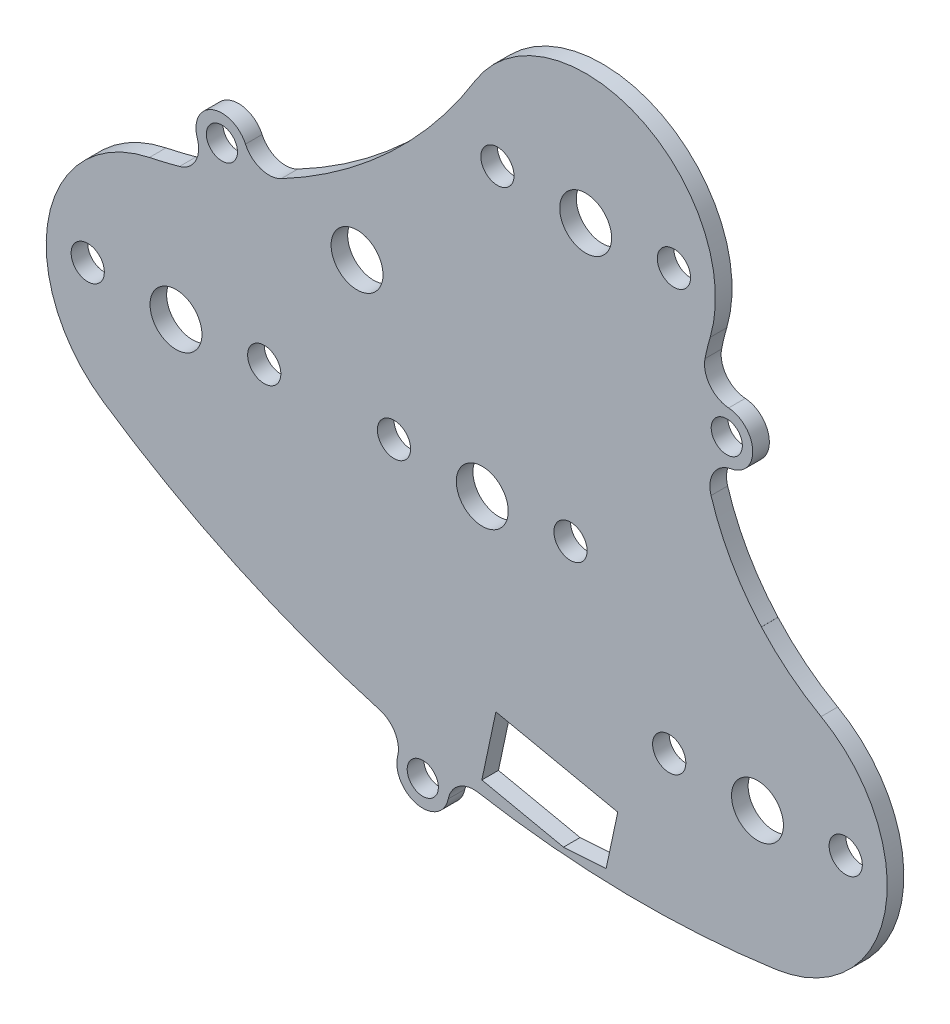
SolidWorks part; units mm, degrees
ref_plane "Front Plane" through (0, 0, 0) normal (0, 0, 1) x (1, 0, 0)
ref_plane "Top Plane" through (0, 0, 0) normal (0, 1, 0) x (1, 0, 0)
ref_plane "Right Plane" through (0, 0, 0) normal (1, 0, 0) x (0, 0, -1)
sketch "Sketch1" plane through (0, 0, 0) normal (0, 0, 1) x (1, 0, 0)
  line L0 (157.8919, 26.2701) -> (191.7747, 29.0915)
  line L1 (157.8919, 26.2701) -> (191.7747, 26.2701)
  line L2 (157.8919, 26.2701) -> (157.8919, 29.0915)
  line L3 (157.8919, 29.0915) -> (191.7747, 29.0915)
  line L4 (191.7747, 26.2701) -> (191.7747, 29.0915)
  line L5 (123.8919, 26.2701) -> (90.0092, 26.2701)
  line L6 (123.8919, 26.2701) -> (123.8919, 29.0915)
  line L7 (123.8919, 29.0915) -> (90.0092, 29.0915)
  line L8 (90.0092, 26.2701) -> (90.0092, 29.0915)
  line L9 (90.0092, 29.0915) -> (123.8919, 26.2701)
  line L10 (168.0919, 58.3601) -> (194.8735, 70.7292)
  line L11 (168.0919, 58.3601) -> (194.8735, 58.3601)
  line L12 (168.0919, 58.3601) -> (168.0919, 70.7292)
  line L13 (168.0919, 70.7292) -> (194.8735, 70.7292)
  line L14 (194.8735, 58.3601) -> (194.8735, 70.7292)
  line L15 (194.8735, 70.7292) -> (224.3587, 70.7292)
  line L16 (194.8735, 70.7292) -> (194.8735, 69.7923)
  line L17 (194.8735, 69.7923) -> (224.3587, 69.7923)
  line L18 (224.3587, 70.7292) -> (224.3587, 69.7923)
  line L19 (224.3587, 69.7923) -> (253.5106, 69.7923)
  line L20 (224.3587, 69.7923) -> (224.3587, 65.2742)
  line L21 (224.3587, 65.2742) -> (253.5106, 65.2742)
  line L22 (253.5106, 69.7923) -> (253.5106, 65.2742)
  line L23 (224.3587, 69.7923) -> (194.8735, 70.7292)
  line L24 (253.5106, 65.2742) -> (224.3587, 69.7923)
  line L25 (170.7502, 87.7401) -> (168.0919, 58.3601)
  line L26 (168.0919, 58.3601) -> (170.7502, 58.3601)
  line L27 (168.0919, 58.3601) -> (168.0919, 87.7401)
  line L28 (168.0919, 87.7401) -> (170.7502, 87.7401)
  line L29 (170.7502, 58.3601) -> (170.7502, 87.7401)
  line L30 (52.9966, 89.4705) -> (24.4119, 82.1791)
  line L31 (24.4119, 82.1791) -> (52.9966, 82.1791)
  line L32 (24.4119, 82.1791) -> (24.4119, 89.4705)
  line L33 (24.4119, 89.4705) -> (52.9966, 89.4705)
  line L34 (52.9966, 82.1791) -> (52.9966, 89.4705)
  line L35 (82.4966, 89.4705) -> (109.0019, 89.4705)
  line L36 (82.4966, 89.4705) -> (82.4966, 76.5201)
  line L37 (82.4966, 76.5201) -> (109.0019, 76.5201)
  line L38 (109.0019, 89.4705) -> (109.0019, 76.5201)
  line L39 (92.4554, 117.2387) -> (82.4966, 117.2387)
  line L40 (92.4554, 117.2387) -> (92.4554, 89.4705)
  line L41 (92.4554, 89.4705) -> (82.4966, 89.4705)
  line L42 (82.4966, 117.2387) -> (82.4966, 89.4705)
  line L43 (92.4554, 117.2387) -> (82.4966, 89.4705)
  line L44 (109.0019, 76.5201) -> (82.4966, 89.4705)
  circle A0 centre (123.8919, 26.2701) radius 14.25
  circle A1 centre (157.8919, 26.2701) radius 14.25
  circle A2 centre (90.0092, 29.0915) radius 14.25
  circle A3 centre (191.7747, 29.0915) radius 14.25
  circle A4 centre (82.4966, 89.4705) radius 11.25
  circle A5 centre (92.4554, 117.2387) radius 11.25
  circle A6 centre (52.9966, 89.4705) radius 11.25
  circle A7 centre (109.0019, 76.5201) radius 11.25
  circle A8 centre (24.4119, 82.1791) radius 11.25
  circle A9 centre (170.7502, 87.7401) radius 11.25
  circle A10 centre (168.0919, 58.3601) radius 11.25
  circle A11 centre (197.5318, 100.1092) radius 11.25
  circle A12 centre (194.8735, 70.7292) radius 11.25
  circle A13 centre (227.0169, 99.1723) radius 11.25
  circle A14 centre (224.3587, 69.7923) radius 11.25
  circle A15 centre (256.1689, 94.6541) radius 11.25
  circle A16 centre (253.5106, 65.2742) radius 11.25
  circle A17 centre (24.4119, 82.1791) radius 12
  circle A18 centre (52.9966, 89.4705) radius 12
  circle A19 centre (92.4554, 117.2387) radius 12
  circle A20 centre (82.4966, 89.4705) radius 12
  circle A21 centre (109.0019, 76.5201) radius 12
  circle A22 centre (168.0919, 58.3601) radius 12
  circle A23 centre (194.8735, 70.7292) radius 12
  circle A24 centre (224.3587, 69.7923) radius 12
  circle A25 centre (253.5106, 65.2742) radius 12
  circle A26 centre (256.1689, 94.6541) radius 12
  circle A27 centre (227.0169, 99.1723) radius 12
  circle A28 centre (197.5318, 100.1092) radius 12
  circle A29 centre (170.7502, 87.7401) radius 12
  circle A30 centre (191.7747, 29.0915) radius 15
  circle A31 centre (157.8919, 26.2701) radius 15
  circle A32 centre (123.8919, 26.2701) radius 15
  circle A33 centre (90.0092, 29.0915) radius 15
  circle A34 centre (173.429, 117.1182) radius 11.25
  circle A35 centre (173.429, 117.1182) radius 12
  dimension "D1" = 28.5
  dimension "D2" = 22.5
  dimension "D3" = 0.75
  dimension "D4" = 0.75
  dimension "D34" = 34
  dimension "D5" = 29.5
  dimension "D6" = 29.5
  dimension "D7" = 29.5
  dimension "D8" = 29.5
  dimension "D9" = 29.5
  dimension "D10" = 29.5
  dimension "D11" = 29.5
  dimension "D12" = 29.5
  dimension "D13" = 29.5
  dimension "D14" = 29.5
  dimension "D15" = 29.5
  dimension "D16" = 29.5
  dimension "D17" = 29.5
  dimension "D18" = 29.5
  dimension "D19" = 34
  dimension "D20" = 34
  dimension "D21" = 32.09
  dimension "D22" = 10.2
  dimension "D23" = 4.76
  dimension "D24" = 4.76
  dimension "D25" = 24.79
  dimension "D26" = 1.82
  dimension "D27" = 8.81
  dimension "D28" = 84.83
  dimension "D29" = 75.69
  dimension "D30" = 70.27
  dimension "D31" = 26.04
  dimension "D32" = 14.89
  dimension "D33" = 50.25
  dimension "D35" = 29.5
  dimension "D36" = 29.5
sketch "Sketch4" plane through (-30.2083, 20.075, 0) normal (0, 0, 1) x (0.9781, -0.2079, 0)
  line L0 (86.1706, 94.1917) -> (105.2206, 75.1417)
  line L1 (67.1206, 94.1917) -> (86.1706, 94.1917)
  line L2 (67.1206, 94.1917) -> (67.1206, 75.1417)
  line L3 (67.1206, 75.1417) -> (86.1706, 75.1417)
  line L4 (86.1706, 94.1917) -> (86.1706, 75.1417)
  line L5 (86.1706, 94.1917) -> (105.2206, 94.1917)
  line L6 (86.1706, 94.1917) -> (86.1706, 75.1417)
  line L7 (86.1706, 75.1417) -> (105.2206, 75.1417)
  line L8 (105.2206, 94.1917) -> (105.2206, 75.1417)
  line L9 (105.2206, 94.1917) -> (124.2706, 94.1917)
  line L10 (105.2206, 94.1917) -> (105.2206, 75.1417)
  line L11 (105.2206, 75.1417) -> (124.2706, 75.1417)
  line L12 (124.2706, 94.1917) -> (124.2706, 75.1417)
  line L13 (86.1706, 94.1917) -> (105.2206, 94.1917)
  line L14 (86.1706, 94.1917) -> (86.1706, 113.2417)
  line L15 (86.1706, 113.2417) -> (105.2206, 113.2417)
  line L16 (105.2206, 94.1917) -> (105.2206, 113.2417)
  line L17 (66.9585, 85.1784) -> (124.4326, 84.1551)
  point P14 (95.6956, 84.6667)
  point P15 (95.6956, 84.6667)
  dimension "D1" = 19.05
sketch "Sketch9" plane through (0, 0, 0) normal (0, 0, 1) x (1, 0, 0)
  line L1 (17.3619, 89.2291) -> (31.4619, 89.2291)
  line L2 (17.3619, 89.2291) -> (17.3619, 75.1291)
  line L3 (17.3619, 75.1291) -> (31.4619, 75.1291)
  line L4 (31.4619, 89.2291) -> (31.4619, 75.1291)
  line L5 (45.9466, 96.5205) -> (60.0466, 96.5205)
  line L6 (45.9466, 96.5205) -> (45.9466, 82.4205)
  line L7 (45.9466, 82.4205) -> (60.0466, 82.4205)
  line L8 (60.0466, 96.5205) -> (60.0466, 82.4205)
  line L9 (75.4466, 96.5205) -> (89.5466, 96.5205)
  line L10 (75.4466, 96.5205) -> (75.4466, 82.4205)
  line L11 (75.4466, 82.4205) -> (89.5466, 82.4205)
  line L12 (89.5466, 96.5205) -> (89.5466, 82.4205)
  line L13 (101.9519, 83.5701) -> (116.0519, 83.5701)
  line L14 (101.9519, 83.5701) -> (101.9519, 69.4701)
  line L15 (101.9519, 69.4701) -> (116.0519, 69.4701)
  line L16 (116.0519, 83.5701) -> (116.0519, 69.4701)
  line L17 (85.4054, 124.2887) -> (99.5054, 124.2887)
  line L18 (85.4054, 124.2887) -> (85.4054, 110.1887)
  line L19 (85.4054, 110.1887) -> (99.5054, 110.1887)
  line L20 (99.5054, 124.2887) -> (99.5054, 110.1887)
  line L21 (82.9592, 36.1415) -> (97.0592, 36.1415)
  line L22 (82.9592, 36.1415) -> (82.9592, 22.0415)
  line L23 (82.9592, 22.0415) -> (97.0592, 22.0415)
  line L24 (97.0592, 36.1415) -> (97.0592, 22.0415)
  line L25 (116.8419, 33.3201) -> (130.9419, 33.3201)
  line L26 (116.8419, 33.3201) -> (116.8419, 19.2201)
  line L27 (116.8419, 19.2201) -> (130.9419, 19.2201)
  line L28 (130.9419, 33.3201) -> (130.9419, 19.2201)
  line L29 (150.8419, 33.3201) -> (164.9419, 33.3201)
  line L30 (150.8419, 33.3201) -> (150.8419, 19.2201)
  line L31 (150.8419, 19.2201) -> (164.9419, 19.2201)
  line L32 (164.9419, 33.3201) -> (164.9419, 19.2201)
  line L33 (184.7247, 36.1415) -> (198.8247, 36.1415)
  line L34 (184.7247, 36.1415) -> (184.7247, 22.0415)
  line L35 (184.7247, 22.0415) -> (198.8247, 22.0415)
  line L36 (198.8247, 36.1415) -> (198.8247, 22.0415)
  line L37 (260.5606, 58.2242) -> (246.4606, 58.2242)
  line L38 (260.5606, 58.2242) -> (260.5606, 72.3242)
  line L39 (260.5606, 72.3242) -> (246.4606, 72.3242)
  line L40 (246.4606, 58.2242) -> (246.4606, 72.3242)
  line L41 (217.3087, 76.8423) -> (231.4087, 76.8423)
  line L42 (217.3087, 76.8423) -> (217.3087, 62.7423)
  line L43 (217.3087, 62.7423) -> (231.4087, 62.7423)
  line L44 (231.4087, 76.8423) -> (231.4087, 62.7423)
  line L45 (187.8235, 77.7792) -> (201.9235, 77.7792)
  line L46 (187.8235, 77.7792) -> (187.8235, 63.6792)
  line L47 (187.8235, 63.6792) -> (201.9235, 63.6792)
  line L48 (201.9235, 77.7792) -> (201.9235, 63.6792)
  line L49 (161.0419, 65.4101) -> (175.1419, 65.4101)
  line L50 (161.0419, 65.4101) -> (161.0419, 51.3101)
  line L51 (161.0419, 51.3101) -> (175.1419, 51.3101)
  line L52 (175.1419, 65.4101) -> (175.1419, 51.3101)
  line L53 (163.7002, 94.7901) -> (177.8002, 94.7901)
  line L54 (163.7002, 94.7901) -> (163.7002, 80.6901)
  line L55 (163.7002, 80.6901) -> (177.8002, 80.6901)
  line L56 (177.8002, 94.7901) -> (177.8002, 80.6901)
  line L57 (190.4818, 107.1592) -> (204.5818, 107.1592)
  line L58 (190.4818, 107.1592) -> (190.4818, 93.0592)
  line L59 (190.4818, 93.0592) -> (204.5818, 93.0592)
  line L60 (204.5818, 107.1592) -> (204.5818, 93.0592)
  line L61 (219.9669, 106.2223) -> (234.0669, 106.2223)
  line L62 (219.9669, 106.2223) -> (219.9669, 92.1223)
  line L63 (219.9669, 92.1223) -> (234.0669, 92.1223)
  line L64 (234.0669, 106.2223) -> (234.0669, 92.1223)
  line L65 (249.1189, 101.7041) -> (263.2189, 101.7041)
  line L66 (249.1189, 101.7041) -> (249.1189, 87.6041)
  line L67 (249.1189, 87.6041) -> (263.2189, 87.6041)
  line L68 (263.2189, 101.7041) -> (263.2189, 87.6041)
  line L69 (166.379, 124.1682) -> (180.479, 124.1682)
  line L70 (166.379, 124.1682) -> (166.379, 110.0682)
  line L71 (166.379, 110.0682) -> (180.479, 110.0682)
  line L72 (180.479, 124.1682) -> (180.479, 110.0682)
  point P72 (24.4119, 89.2291)
  point P74 (52.9966, 96.5205)
  point P76 (82.4966, 96.5205)
  point P78 (92.4554, 124.2887)
  point P80 (109.0019, 83.5701)
  point P82 (90.0092, 36.1415)
  point P84 (123.8919, 33.3201)
  point P86 (157.8919, 33.3201)
  point P88 (191.7747, 36.1415)
  point P90 (168.0919, 65.4101)
  point P92 (170.7502, 94.7901)
  point P94 (173.429, 124.1682)
  point P96 (197.5318, 107.1592)
  point P98 (227.0169, 106.2223)
  point P100 (256.1689, 101.7041)
  point P102 (194.8735, 77.7792)
  point P104 (224.3587, 76.8423)
  point P106 (253.5106, 72.3242)
  point P108 (17.3619, 82.1791)
  point P109 (45.9466, 89.4705)
  point P110 (75.4466, 89.4705)
  point P111 (101.9519, 76.5201)
  point P112 (85.4054, 117.2387)
  point P113 (82.9592, 29.0915)
  point P114 (116.8419, 26.2701)
  point P115 (150.8419, 26.2701)
  point P116 (184.7247, 29.0915)
  point P118 (161.0419, 58.3601)
  point P119 (187.8235, 70.7292)
  point P120 (217.3087, 69.7923)
  point P121 (246.4606, 65.2742)
  point P122 (163.7002, 87.7401)
  point P123 (190.4818, 100.1092)
  point P124 (219.9669, 99.1723)
  point P125 (249.1189, 94.6541)
  point P126 (166.379, 117.1182)
  dimension "D1" = 14.1
sketch "Sketch10" plane through (-22.0981, 19.3454, 0) normal (0, 0, 1) x (0.9781, -0.2079, 0)
  line L1 (61.5108, 90.7441) -> (75.6108, 90.7441)
  line L2 (61.5108, 90.7441) -> (61.5108, 76.6441)
  line L3 (61.5108, 76.6441) -> (75.6108, 76.6441)
  line L4 (75.6108, 90.7441) -> (75.6108, 76.6441)
  line L5 (80.5608, 90.7441) -> (94.6608, 90.7441)
  line L6 (80.5608, 90.7441) -> (80.5608, 76.6441)
  line L7 (80.5608, 76.6441) -> (94.6608, 76.6441)
  line L8 (94.6608, 90.7441) -> (94.6608, 76.6441)
  line L9 (99.6108, 90.7441) -> (113.7108, 90.7441)
  line L10 (99.6108, 90.7441) -> (99.6108, 76.6441)
  line L11 (99.6108, 76.6441) -> (113.7108, 76.6441)
  line L12 (113.7108, 90.7441) -> (113.7108, 76.6441)
  line L13 (80.5608, 109.7941) -> (94.6608, 109.7941)
  line L14 (80.5608, 109.7941) -> (80.5608, 95.6941)
  line L15 (80.5608, 95.6941) -> (94.6608, 95.6941)
  line L16 (94.6608, 109.7941) -> (94.6608, 95.6941)
  line L17 (50.5121, 89.6359) -> (53.4436, 75.8441) construction
  line L18 (59.0358, 93.2191) -> (78.0858, 93.2191) construction
  line L19 (78.0858, 112.2691) -> (97.1358, 112.2691) construction
  line L20 (97.1358, 93.2191) -> (116.1858, 93.2191) construction
  line L21 (78.0858, 93.2191) -> (78.0858, 112.2691) construction
  line L23 (59.0358, 93.2191) -> (59.0358, 74.1691) construction
  point P16 (75.6108, 83.6941)
  point P17 (94.6608, 83.6941)
  point P18 (113.7108, 83.6941)
  point P19 (87.6108, 90.7441)
  point P20 (87.6108, 109.7941)
  point P23 (68.5608, 90.7441)
  point P26 (68.5608, 93.2191)
  point P29 (87.6108, 112.2691)
  point P30 (106.6608, 90.7441)
  point P33 (106.6608, 93.2191)
  point P34 (80.5608, 102.7441)
  point P37 (78.0858, 102.7441)
  point P42 (59.0358, 83.6941)
  point P43 (61.5108, 83.6941)
sketch "Sketch14" plane through (0, 0, 0) normal (0, 0, 1) x (1, 0, 0)
  line L0 (165.1144, 80.6901) -> (163.7002, 82.1043)
  line L1 (163.7002, 93.3758) -> (165.1144, 94.7901)
  line L2 (177.8002, 93.3758) -> (176.386, 94.7901)
  line L3 (179.0648, 110.0682) -> (180.479, 111.4824)
  line L4 (166.379, 111.4824) -> (167.7932, 110.0682)
  line L5 (166.379, 122.754) -> (167.7932, 124.1682)
  line L6 (179.0648, 124.1682) -> (180.479, 122.754)
  line L7 (203.1676, 93.0592) -> (204.5818, 94.4734)
  line L8 (17.3619, 89.2291) -> (17.3619, 75.1291) construction
  line L9 (17.3619, 89.2291) -> (31.4619, 89.2291) construction
  line L10 (17.3619, 87.8149) -> (18.7761, 89.2291)
  line L11 (17.3619, 75.1291) -> (31.4619, 75.1291) construction
  line L12 (31.4619, 89.2291) -> (31.4619, 75.1291) construction
  line L13 (45.9466, 96.5205) -> (60.0466, 96.5205) construction
  line L14 (60.0466, 96.5205) -> (60.0466, 82.4205) construction
  line L15 (45.9466, 96.5205) -> (45.9466, 82.4205) construction
  line L16 (45.9466, 82.4205) -> (60.0466, 82.4205) construction
  line L17 (85.4054, 124.2887) -> (85.4054, 110.1887) construction
  line L18 (85.4054, 124.2887) -> (99.5054, 124.2887) construction
  line L19 (99.5054, 124.2887) -> (99.5054, 110.1887) construction
  line L20 (85.4054, 110.1887) -> (99.5054, 110.1887) construction
  line L21 (101.9519, 83.5701) -> (101.9519, 69.4701) construction
  line L22 (101.9519, 83.5701) -> (116.0519, 83.5701) construction
  line L23 (116.0519, 83.5701) -> (116.0519, 69.4701) construction
  line L24 (101.9519, 69.4701) -> (116.0519, 69.4701) construction
  line L25 (91.2712, 73.6044) -> (105.0631, 70.6729) construction
  line L26 (107.9947, 84.4647) -> (105.0631, 70.6729) construction
  line L27 (94.2028, 87.3963) -> (107.9947, 84.4647) construction
  line L28 (94.2028, 87.3963) -> (91.2712, 73.6044) construction
  line L29 (72.6375, 77.5651) -> (86.4294, 74.6336) construction
  line L30 (89.361, 88.4255) -> (86.4294, 74.6336) construction
  line L31 (75.5691, 91.357) -> (89.361, 88.4255) construction
  line L32 (75.5691, 91.357) -> (72.6375, 77.5651) construction
  line L33 (56.9354, 95.3177) -> (54.0038, 81.5259) construction
  line L34 (56.9354, 95.3177) -> (70.7273, 92.3862) construction
  line L35 (70.7273, 92.3862) -> (67.7957, 78.5943) construction
  line L36 (54.0038, 81.5259) -> (67.7957, 78.5943) construction
  line L37 (76.5983, 96.1988) -> (90.3901, 93.2673) construction
  line L38 (93.3217, 107.0592) -> (90.3901, 93.2673) construction
  line L39 (79.5298, 109.9907) -> (76.5983, 96.1988) construction
  line L40 (79.5298, 109.9907) -> (93.3217, 107.0592) construction
  line L41 (82.9592, 36.1415) -> (82.9592, 22.0415) construction
  line L42 (82.9592, 36.1415) -> (97.0592, 36.1415) construction
  line L43 (82.9592, 22.0415) -> (97.0592, 22.0415) construction
  line L44 (97.0592, 36.1415) -> (97.0592, 22.0415) construction
  line L45 (116.8419, 33.3201) -> (116.8419, 19.2201) construction
  line L46 (116.8419, 33.3201) -> (130.9419, 33.3201) construction
  line L47 (116.8419, 19.2201) -> (130.9419, 19.2201) construction
  line L48 (130.9419, 33.3201) -> (130.9419, 19.2201) construction
  line L49 (150.8419, 33.3201) -> (150.8419, 19.2201) construction
  line L50 (150.8419, 33.3201) -> (164.9419, 33.3201) construction
  line L51 (164.9419, 33.3201) -> (164.9419, 19.2201) construction
  line L52 (150.8419, 19.2201) -> (164.9419, 19.2201) construction
  line L53 (184.7247, 36.1415) -> (184.7247, 22.0415) construction
  line L54 (184.7247, 22.0415) -> (198.8247, 22.0415) construction
  line L55 (198.8247, 36.1415) -> (198.8247, 22.0415) construction
  line L56 (184.7247, 36.1415) -> (198.8247, 36.1415) construction
  line L57 (161.0419, 65.4101) -> (175.1419, 65.4101) construction
  line L58 (175.1419, 65.4101) -> (175.1419, 51.3101) construction
  line L59 (161.0419, 51.3101) -> (175.1419, 51.3101) construction
  line L60 (161.0419, 65.4101) -> (161.0419, 51.3101) construction
  line L61 (187.8235, 77.7792) -> (187.8235, 63.6792) construction
  line L62 (187.8235, 77.7792) -> (201.9235, 77.7792) construction
  line L63 (187.8235, 63.6792) -> (201.9235, 63.6792) construction
  line L64 (201.9235, 77.7792) -> (201.9235, 63.6792) construction
  line L65 (217.3087, 76.8423) -> (217.3087, 62.7423) construction
  line L66 (217.3087, 76.8423) -> (231.4087, 76.8423) construction
  line L67 (231.4087, 76.8423) -> (231.4087, 62.7423) construction
  line L68 (217.3087, 62.7423) -> (231.4087, 62.7423) construction
  line L69 (260.5606, 58.2242) -> (246.4606, 58.2242) construction
  line L70 (260.5606, 58.2242) -> (260.5606, 72.3242) construction
  line L71 (246.4606, 58.2242) -> (246.4606, 72.3242) construction
  line L72 (260.5606, 72.3242) -> (246.4606, 72.3242) construction
  line L73 (249.1189, 101.7041) -> (263.2189, 101.7041) construction
  line L74 (263.2189, 101.7041) -> (263.2189, 87.6041) construction
  line L75 (249.1189, 87.6041) -> (263.2189, 87.6041) construction
  line L76 (249.1189, 101.7041) -> (249.1189, 87.6041) construction
  line L77 (219.9669, 106.2223) -> (219.9669, 92.1223) construction
  line L78 (219.9669, 106.2223) -> (234.0669, 106.2223) construction
  line L79 (234.0669, 106.2223) -> (234.0669, 92.1223) construction
  line L80 (219.9669, 92.1223) -> (234.0669, 92.1223) construction
  line L81 (190.4818, 107.1592) -> (204.5818, 107.1592) construction
  line L82 (204.5818, 107.1592) -> (204.5818, 93.0592) construction
  line L83 (190.4818, 93.0592) -> (204.5818, 93.0592) construction
  line L84 (190.4818, 107.1592) -> (190.4818, 93.0592) construction
  line L85 (163.7002, 94.7901) -> (177.8002, 94.7901) construction
  line L86 (177.8002, 94.7901) -> (177.8002, 80.6901) construction
  line L87 (163.7002, 80.6901) -> (177.8002, 80.6901) construction
  line L88 (163.7002, 94.7901) -> (163.7002, 80.6901) construction
  line L89 (180.479, 124.1682) -> (180.479, 110.0682) construction
  line L90 (166.379, 110.0682) -> (180.479, 110.0682) construction
  line L91 (166.379, 124.1682) -> (166.379, 110.0682) construction
  line L92 (166.379, 124.1682) -> (180.479, 124.1682) construction
  line L93 (17.3619, 76.5433) -> (18.7761, 75.1291)
  line L94 (30.0477, 75.1291) -> (31.4619, 76.5433)
  line L95 (31.4619, 87.8149) -> (30.0477, 89.2291)
  line L96 (45.9466, 95.1063) -> (47.3608, 96.5205)
  line L97 (45.9466, 83.8347) -> (47.3608, 82.4205)
  line L98 (54.2979, 82.9092) -> (55.3871, 81.2318)
  line L99 (58.6323, 82.4205) -> (60.0466, 83.8347)
  line L100 (56.6413, 93.9344) -> (58.3187, 95.0237)
  line L101 (58.6323, 96.5205) -> (60.0466, 95.1063)
  line L102 (69.3439, 92.6802) -> (70.4332, 91.0029)
  line L103 (68.0897, 79.9776) -> (66.4124, 78.8883)
  line L104 (75.2751, 89.9737) -> (76.9524, 91.063)
  line L105 (72.9316, 78.9484) -> (74.0208, 77.2711)
  line L106 (85.0461, 74.9276) -> (86.7234, 76.0169)
  line L107 (89.0669, 87.0421) -> (87.9777, 88.7195)
  line L108 (89.0068, 93.5613) -> (90.6842, 94.6506)
  line L109 (76.8923, 97.5822) -> (77.9816, 95.9048)
  line L110 (91.9384, 107.3532) -> (93.0277, 105.6759)
  line L111 (79.2358, 108.6074) -> (80.9131, 109.6967)
  line L112 (85.4054, 111.6029) -> (86.8196, 110.1887)
  line L113 (98.0912, 110.1887) -> (99.5054, 111.6029)
  line L114 (98.0912, 124.2887) -> (99.5054, 122.8745)
  line L115 (85.4054, 122.8745) -> (86.8196, 124.2887)
  line L116 (93.9088, 86.013) -> (95.5861, 87.1023)
  line L117 (91.5653, 74.9877) -> (92.6546, 73.3104)
  line L118 (103.6798, 70.9669) -> (105.3572, 72.0562)
  line L119 (106.6114, 84.7588) -> (107.7006, 83.0814)
  line L120 (101.9519, 82.1559) -> (103.3662, 83.5701)
  line L121 (101.9519, 70.8843) -> (103.3662, 69.4701)
  line L122 (114.6377, 69.4701) -> (116.0519, 70.8843)
  line L123 (116.0519, 82.1559) -> (114.6377, 83.5701)
  line L124 (82.9592, 34.7272) -> (84.3734, 36.1415)
  line L125 (82.9592, 23.4557) -> (84.3734, 22.0415)
  line L126 (95.645, 22.0415) -> (97.0592, 23.4557)
  line L127 (97.0592, 34.7272) -> (95.645, 36.1415)
  line L128 (116.8419, 31.9059) -> (118.2562, 33.3201)
  line L129 (116.8419, 20.6343) -> (118.2562, 19.2201)
  line L130 (129.5277, 19.2201) -> (130.9419, 20.6343)
  line L131 (130.9419, 31.9059) -> (129.5277, 33.3201)
  line L132 (150.8419, 31.9059) -> (152.2562, 33.3201)
  line L133 (150.8419, 20.6343) -> (152.2562, 19.2201)
  line L134 (163.5277, 19.2201) -> (164.9419, 20.6343)
  line L135 (164.9419, 31.9059) -> (163.5277, 33.3201)
  line L136 (184.7247, 34.7272) -> (186.1389, 36.1415)
  line L137 (184.7247, 23.4557) -> (186.1389, 22.0415)
  line L138 (197.4105, 22.0415) -> (198.8247, 23.4557)
  line L139 (198.8247, 34.7272) -> (197.4105, 36.1415)
  line L140 (173.7277, 51.3101) -> (175.1419, 52.7243)
  line L141 (161.0419, 52.7243) -> (162.4562, 51.3101)
  line L142 (161.0419, 63.9959) -> (162.4562, 65.4101)
  line L143 (173.7277, 65.4101) -> (175.1419, 63.9959)
  line L144 (187.8235, 65.0934) -> (189.2378, 63.6792)
  line L145 (200.5093, 63.6792) -> (201.9235, 65.0934)
  line L146 (200.5093, 77.7792) -> (201.9235, 76.365)
  line L147 (187.8235, 76.365) -> (189.2378, 77.7792)
  line L148 (176.386, 80.6901) -> (177.8002, 82.1043)
  line L149 (204.5818, 105.745) -> (203.1676, 107.1592)
  line L150 (191.896, 107.1592) -> (190.4818, 105.745)
  line L151 (190.4818, 94.4734) -> (191.896, 93.0592)
  line L152 (219.9669, 104.8081) -> (221.3812, 106.2223)
  line L153 (232.6527, 106.2223) -> (234.0669, 104.8081)
  line L154 (234.0669, 93.5365) -> (232.6527, 92.1223)
  line L155 (219.9669, 93.5365) -> (221.3812, 92.1223)
  line L156 (229.9944, 76.8423) -> (231.4087, 75.4281)
  line L157 (217.3087, 75.4281) -> (218.7229, 76.8423)
  line L158 (217.3087, 64.1565) -> (218.7229, 62.7423)
  line L159 (229.9944, 62.7423) -> (231.4087, 64.1565)
  line L160 (259.1464, 72.3242) -> (260.5606, 70.9099)
  line L161 (246.4606, 70.9099) -> (247.8748, 72.3242)
  line L162 (259.1464, 58.2242) -> (260.5606, 59.6384)
  line L163 (247.8748, 58.2242) -> (246.4606, 59.6384)
  line L164 (261.8047, 87.6041) -> (263.2189, 89.0183)
  line L165 (249.1189, 89.0183) -> (250.5331, 87.6041)
  line L166 (249.1189, 100.2899) -> (250.5331, 101.7041)
  line L167 (261.8047, 101.7041) -> (263.2189, 100.2899)
  line L168 (75.4466, 96.5205) -> (75.4466, 82.4205) construction
  line L169 (75.4466, 96.5205) -> (89.5466, 96.5205) construction
  line L170 (89.5466, 96.5205) -> (89.5466, 82.4205) construction
  line L171 (75.4466, 82.4205) -> (89.5466, 82.4205) construction
  line L172 (76.8608, 96.5205) -> (75.4466, 95.1063)
  line L173 (88.1323, 96.5205) -> (89.5466, 95.1063)
  line L174 (89.5466, 83.8347) -> (88.1323, 82.4205)
  line L175 (75.4466, 83.8347) -> (76.8608, 82.4205)
  arc A0 (17.3619, 87.8149) -> (18.7761, 89.2291) centre (18.069, 88.522) cw
  arc A1 (18.7761, 75.1291) -> (17.3619, 76.5433) centre (18.069, 75.8362) cw
  arc A2 (31.4619, 76.5433) -> (30.0477, 75.1291) centre (30.7548, 75.8362) cw
  arc A3 (30.0477, 89.2291) -> (31.4619, 87.8149) centre (30.7548, 88.522) cw
  arc A4 (58.6323, 96.5205) -> (60.0466, 95.1063) centre (59.3394, 95.8134) cw
  arc A5 (45.9466, 95.1063) -> (47.3608, 96.5205) centre (46.6537, 95.8134) cw
  arc A6 (47.3608, 82.4205) -> (45.9466, 83.8347) centre (46.6537, 83.1276) cw
  arc A7 (60.0466, 83.8347) -> (58.6323, 82.4205) centre (59.3394, 83.1276) cw
  arc A8 (85.4054, 122.8745) -> (86.8196, 124.2887) centre (86.1125, 123.5816) cw
  arc A9 (98.0912, 124.2887) -> (99.5054, 122.8745) centre (98.7983, 123.5816) cw
  arc A10 (99.5054, 111.6029) -> (98.0912, 110.1887) centre (98.7983, 110.8958) cw
  arc A11 (85.4054, 111.6029) -> (86.8196, 110.1887) centre (86.1125, 110.8958) ccw
  arc A12 (101.9519, 82.1559) -> (103.3662, 83.5701) centre (102.6591, 82.863) cw
  arc A13 (114.6377, 83.5701) -> (116.0519, 82.1559) centre (115.3448, 82.863) cw
  arc A14 (116.0519, 70.8843) -> (114.6377, 69.4701) centre (115.3448, 70.1772) cw
  arc A15 (101.9519, 70.8843) -> (103.3662, 69.4701) centre (102.6591, 70.1772) ccw
  arc A16 (103.6798, 70.9669) -> (105.3572, 72.0562) centre (104.5185, 71.5115) ccw
  arc A17 (106.6114, 84.7588) -> (107.7006, 83.0814) centre (107.156, 83.9201) cw
  arc A18 (93.9088, 86.013) -> (95.5861, 87.1023) centre (94.7474, 86.5576) cw
  arc A19 (91.5653, 74.9877) -> (92.6546, 73.3104) centre (92.1099, 74.1491) ccw
  arc A20 (85.0461, 74.9276) -> (86.7234, 76.0169) centre (85.8848, 75.4722) ccw
  arc A21 (87.9777, 88.7195) -> (89.0669, 87.0421) centre (88.5223, 87.8808) cw
  arc A22 (75.2751, 89.9737) -> (76.9524, 91.063) centre (76.1137, 90.5183) cw
  arc A23 (72.9316, 78.9484) -> (74.0208, 77.2711) centre (73.4762, 78.1098) ccw
  arc A24 (56.6413, 93.9344) -> (58.3187, 95.0237) centre (57.48, 94.4791) cw
  arc A25 (69.3439, 92.6802) -> (70.4332, 91.0029) centre (69.8886, 91.8415) cw
  arc A26 (68.0897, 79.9776) -> (66.4124, 78.8883) centre (67.2511, 79.433) cw
  arc A27 (54.2979, 82.9092) -> (55.3871, 81.2318) centre (54.8425, 82.0705) ccw
  arc A28 (89.0068, 93.5613) -> (90.6842, 94.6506) centre (89.8455, 94.106) ccw
  arc A29 (76.8923, 97.5822) -> (77.9816, 95.9048) centre (77.4369, 96.7435) ccw
  arc A30 (79.2358, 108.6074) -> (80.9131, 109.6967) centre (80.0744, 109.1521) cw
  arc A31 (91.9384, 107.3532) -> (93.0277, 105.6759) centre (92.483, 106.5145) cw
  arc A32 (82.9592, 34.7272) -> (84.3734, 36.1415) centre (83.6663, 35.4344) cw
  arc A33 (82.9592, 23.4557) -> (84.3734, 22.0415) centre (83.6663, 22.7486) ccw
  arc A34 (95.645, 22.0415) -> (97.0592, 23.4557) centre (96.3521, 22.7486) ccw
  arc A35 (95.645, 36.1415) -> (97.0592, 34.7272) centre (96.3521, 35.4344) cw
  arc A36 (116.8419, 31.9059) -> (118.2562, 33.3201) centre (117.5491, 32.613) cw
  arc A37 (116.8419, 20.6343) -> (118.2562, 19.2201) centre (117.5491, 19.9272) ccw
  arc A38 (129.5277, 19.2201) -> (130.9419, 20.6343) centre (130.2348, 19.9272) ccw
  arc A39 (129.5277, 33.3201) -> (130.9419, 31.9059) centre (130.2348, 32.613) cw
  arc A40 (150.8419, 31.9059) -> (152.2562, 33.3201) centre (151.5491, 32.613) cw
  arc A41 (163.5277, 33.3201) -> (164.9419, 31.9059) centre (164.2348, 32.613) cw
  arc A42 (164.9419, 20.6343) -> (163.5277, 19.2201) centre (164.2348, 19.9272) cw
  arc A43 (150.8419, 20.6343) -> (152.2562, 19.2201) centre (151.5491, 19.9272) ccw
  arc A44 (184.7247, 23.4557) -> (186.1389, 22.0415) centre (185.4318, 22.7486) ccw
  arc A45 (197.4105, 22.0415) -> (198.8247, 23.4557) centre (198.1176, 22.7486) ccw
  arc A46 (197.4105, 36.1415) -> (198.8247, 34.7272) centre (198.1176, 35.4344) cw
  arc A47 (184.7247, 34.7272) -> (186.1389, 36.1415) centre (185.4318, 35.4344) cw
  arc A48 (173.7277, 65.4101) -> (175.1419, 63.9959) centre (174.4348, 64.703) cw
  arc A49 (175.1419, 52.7243) -> (173.7277, 51.3101) centre (174.4348, 52.0172) cw
  arc A50 (161.0419, 52.7243) -> (162.4562, 51.3101) centre (161.7491, 52.0172) ccw
  arc A51 (161.0419, 63.9959) -> (162.4562, 65.4101) centre (161.7491, 64.703) cw
  arc A52 (187.8235, 76.365) -> (189.2378, 77.7792) centre (188.5306, 77.0721) cw
  arc A53 (187.8235, 65.0934) -> (189.2378, 63.6792) centre (188.5306, 64.3863) ccw
  arc A54 (200.5093, 63.6792) -> (201.9235, 65.0934) centre (201.2164, 64.3863) ccw
  arc A55 (200.5093, 77.7792) -> (201.9235, 76.365) centre (201.2164, 77.0721) cw
  arc A56 (217.3087, 75.4281) -> (218.7229, 76.8423) centre (218.0158, 76.1352) cw
  arc A57 (229.9944, 76.8423) -> (231.4087, 75.4281) centre (230.7016, 76.1352) cw
  arc A58 (231.4087, 64.1565) -> (229.9944, 62.7423) centre (230.7016, 63.4494) cw
  arc A59 (217.3087, 64.1565) -> (218.7229, 62.7423) centre (218.0158, 63.4494) ccw
  arc A60 (259.1464, 58.2242) -> (260.5606, 59.6384) centre (259.8535, 58.9313) ccw
  arc A61 (246.4606, 59.6384) -> (247.8748, 58.2242) centre (247.1677, 58.9313) ccw
  arc A62 (246.4606, 70.9099) -> (247.8748, 72.3242) centre (247.1677, 71.617) cw
  arc A63 (259.1464, 72.3242) -> (260.5606, 70.9099) centre (259.8535, 71.617) cw
  arc A64 (261.8047, 101.7041) -> (263.2189, 100.2899) centre (262.5118, 100.997) cw
  arc A65 (263.2189, 89.0183) -> (261.8047, 87.6041) centre (262.5118, 88.3112) cw
  arc A66 (250.5331, 87.6041) -> (249.1189, 89.0183) centre (249.826, 88.3112) cw
  arc A67 (249.1189, 100.2899) -> (250.5331, 101.7041) centre (249.826, 100.997) cw
  arc A68 (219.9669, 104.8081) -> (221.3812, 106.2223) centre (220.674, 105.5152) cw
  arc A69 (232.6527, 106.2223) -> (234.0669, 104.8081) centre (233.3598, 105.5152) cw
  arc A70 (234.0669, 93.5365) -> (232.6527, 92.1223) centre (233.3598, 92.8294) cw
  arc A71 (221.3812, 92.1223) -> (219.9669, 93.5365) centre (220.674, 92.8294) cw
  arc A72 (203.1676, 107.1592) -> (204.5818, 105.745) centre (203.8747, 106.4521) cw
  arc A73 (204.5818, 94.4734) -> (203.1676, 93.0592) centre (203.8747, 93.7663) cw
  arc A74 (191.896, 93.0592) -> (190.4818, 94.4734) centre (191.1889, 93.7663) cw
  arc A75 (190.4818, 105.745) -> (191.896, 107.1592) centre (191.1889, 106.4521) cw
  arc A76 (176.386, 94.7901) -> (177.8002, 93.3758) centre (177.0931, 94.0829) cw
  arc A77 (177.8002, 82.1043) -> (176.386, 80.6901) centre (177.0931, 81.3972) cw
  arc A78 (165.1144, 80.6901) -> (163.7002, 82.1043) centre (164.4073, 81.3972) cw
  arc A79 (163.7002, 93.3758) -> (165.1144, 94.7901) centre (164.4073, 94.0829) cw
  arc A80 (180.479, 111.4824) -> (179.0648, 110.0682) centre (179.7719, 110.7753) cw
  arc A81 (167.7932, 110.0682) -> (166.379, 111.4824) centre (167.0861, 110.7753) cw
  arc A82 (179.0648, 124.1682) -> (180.479, 122.754) centre (179.7719, 123.4611) cw
  arc A83 (166.379, 122.754) -> (167.7932, 124.1682) centre (167.0861, 123.4611) cw
  arc A84 (75.4466, 95.1063) -> (76.8608, 96.5205) centre (76.1537, 95.8134) cw
  arc A85 (88.1323, 96.5205) -> (89.5466, 95.1063) centre (88.8394, 95.8134) cw
  arc A86 (89.5466, 83.8347) -> (88.1323, 82.4205) centre (88.8394, 83.1276) cw
  arc A87 (76.8608, 82.4205) -> (75.4466, 83.8347) centre (76.1537, 83.1276) cw
  dimension "D1" = 45
  dimension "D2" = 1
  dimension "D71" = 45
  dimension "D3" = 45
  dimension "D4" = 45
  dimension "D5" = 45
  dimension "D6" = 45
  dimension "D7" = 45
  dimension "D8" = 45
  dimension "D9" = 45
  dimension "D10" = 45
  dimension "D11" = 45
  dimension "D12" = 45
  dimension "D13" = 45
  dimension "D14" = 45
  dimension "D15" = 45
  dimension "D16" = 45
  dimension "D17" = 45
  dimension "D18" = 45
  dimension "D19" = 45
  dimension "D20" = 45
  dimension "D21" = 45
  dimension "D22" = 45
  dimension "D23" = 45
  dimension "D24" = 45
  dimension "D25" = 45
  dimension "D26" = 45
  dimension "D27" = 45
  dimension "D28" = 45
  dimension "D29" = 45
  dimension "D30" = 45
  dimension "D31" = 45
  dimension "D32" = 45
  dimension "D33" = 45
  dimension "D34" = 45
  dimension "D35" = 45
  dimension "D36" = 45
  dimension "D37" = 45
  dimension "D38" = 45
  dimension "D39" = 45
  dimension "D40" = 45
  dimension "D41" = 45
  dimension "D42" = 45
  dimension "D43" = 45
  dimension "D44" = 45
  dimension "D45" = 45
  dimension "D46" = 45
  dimension "D47" = 45
  dimension "D48" = 45
  dimension "D49" = 45
  dimension "D50" = 45
  dimension "D51" = 45
  dimension "D52" = 45
  dimension "D53" = 45
  dimension "D54" = 45
  dimension "D55" = 45
  dimension "D56" = 45
  dimension "D57" = 45
  dimension "D58" = 45
  dimension "D59" = 45
  dimension "D60" = 45
  dimension "D61" = 45
  dimension "D62" = 45
  dimension "D63" = 45
  dimension "D64" = 45
  dimension "D65" = 45
  dimension "D66" = 45
  dimension "D67" = 45
  dimension "D68" = 45
  dimension "D69" = 45
  dimension "D70" = 45
  dimension "D72" = 45
  dimension "D73" = 45
  dimension "D74" = 45
  dimension "D75" = 45
  dimension "D76" = 45
  dimension "D77" = 45
  dimension "D78" = 45
  dimension "D79" = 45
  dimension "D80" = 45
  dimension "D81" = 45
  dimension "D82" = 45
  dimension "D83" = 45
  dimension "D84" = 45
  dimension "D85" = 45
  dimension "D86" = 45
  dimension "D87" = 45
  dimension "D88" = 45
  dimension "D89" = 45
sketch "Sketch16" plane through (0, 0, 0) normal (0, 0, 1) x (1, 0, 0)
  line L0 (81.5092, 30.6915) -> (98.5092, 30.6915)
  line L5 (17.3619, 89.2291) -> (17.3619, 75.1291) construction
  line L6 (81.5092, 30.6915) -> (81.5092, 27.4915)
  line L7 (17.3619, 75.1291) -> (31.4619, 75.1291) construction
  line L8 (15.9119, 83.7791) -> (32.9119, 83.7791)
  line L9 (15.9119, 83.7791) -> (15.9119, 80.5791)
  line L10 (15.9119, 80.5791) -> (32.9119, 80.5791)
  line L11 (32.9119, 83.7791) -> (32.9119, 80.5791)
  line L12 (81.5092, 27.4915) -> (98.5092, 27.4915)
  line L13 (98.5092, 30.6915) -> (98.5092, 27.4915)
  line L14 (115.3919, 27.8701) -> (132.3919, 27.8701)
  line L15 (115.3919, 27.8701) -> (115.3919, 24.6701)
  line L16 (115.3919, 24.6701) -> (132.3919, 24.6701)
  line L17 (132.3919, 27.8701) -> (132.3919, 24.6701)
  line L18 (149.3919, 27.8701) -> (166.3919, 27.8701)
  line L19 (149.3919, 27.8701) -> (149.3919, 24.6701)
  line L20 (149.3919, 24.6701) -> (166.3919, 24.6701)
  line L21 (166.3919, 27.8701) -> (166.3919, 24.6701)
  line L22 (183.2747, 30.6915) -> (200.2747, 30.6915)
  line L23 (183.2747, 30.6915) -> (183.2747, 27.4915)
  line L24 (183.2747, 27.4915) -> (200.2747, 27.4915)
  line L25 (200.2747, 30.6915) -> (200.2747, 27.4915)
  line L26 (44.4966, 91.5705) -> (61.4966, 91.5705)
  line L27 (44.4966, 91.5705) -> (44.4966, 88.3705)
  line L28 (44.4966, 88.3705) -> (61.4966, 88.3705)
  line L29 (61.4966, 91.5705) -> (61.4966, 88.3705)
  line L30 (73.9966, 91.5705) -> (90.9966, 91.5705)
  line L31 (73.9966, 91.5705) -> (73.9966, 88.3705)
  line L32 (73.9966, 88.3705) -> (90.9966, 88.3705)
  line L33 (90.9966, 91.5705) -> (90.9966, 88.3705)
  line L34 (100.5019, 78.6201) -> (117.5019, 78.6201)
  line L35 (100.5019, 78.6201) -> (100.5019, 75.4201)
  line L36 (100.5019, 75.4201) -> (117.5019, 75.4201)
  line L37 (117.5019, 78.6201) -> (117.5019, 75.4201)
  line L38 (83.9554, 119.3387) -> (100.9554, 119.3387)
  line L39 (83.9554, 119.3387) -> (83.9554, 116.1387)
  line L40 (83.9554, 116.1387) -> (100.9554, 116.1387)
  line L41 (100.9554, 119.3387) -> (100.9554, 116.1387)
  line L42 (164.929, 118.7182) -> (181.929, 118.7182)
  line L43 (164.929, 118.7182) -> (164.929, 115.5182)
  line L44 (164.929, 115.5182) -> (181.929, 115.5182)
  line L45 (181.929, 118.7182) -> (181.929, 115.5182)
  line L46 (162.2502, 89.3401) -> (179.2502, 89.3401)
  line L47 (162.2502, 89.3401) -> (162.2502, 86.1401)
  line L48 (162.2502, 86.1401) -> (179.2502, 86.1401)
  line L49 (179.2502, 89.3401) -> (179.2502, 86.1401)
  line L50 (189.0318, 101.7092) -> (206.0318, 101.7092)
  line L51 (189.0318, 101.7092) -> (189.0318, 98.5092)
  line L52 (189.0318, 98.5092) -> (206.0318, 98.5092)
  line L53 (206.0318, 101.7092) -> (206.0318, 98.5092)
  line L54 (159.5919, 59.9601) -> (176.5919, 59.9601)
  line L55 (159.5919, 59.9601) -> (159.5919, 56.7601)
  line L56 (159.5919, 56.7601) -> (176.5919, 56.7601)
  line L57 (176.5919, 59.9601) -> (176.5919, 56.7601)
  line L58 (186.3735, 72.3292) -> (203.3735, 72.3292)
  line L59 (186.3735, 72.3292) -> (186.3735, 69.1292)
  line L60 (186.3735, 69.1292) -> (203.3735, 69.1292)
  line L61 (203.3735, 72.3292) -> (203.3735, 69.1292)
  line L62 (218.5169, 100.7723) -> (235.5169, 100.7723)
  line L63 (218.5169, 100.7723) -> (218.5169, 97.5723)
  line L64 (218.5169, 97.5723) -> (235.5169, 97.5723)
  line L65 (235.5169, 100.7723) -> (235.5169, 97.5723)
  line L66 (215.8587, 71.3923) -> (232.8587, 71.3923)
  line L67 (215.8587, 71.3923) -> (215.8587, 68.1923)
  line L68 (215.8587, 68.1923) -> (232.8587, 68.1923)
  line L69 (232.8587, 71.3923) -> (232.8587, 68.1923)
  line L70 (247.6689, 96.2541) -> (264.6689, 96.2541)
  line L71 (247.6689, 96.2541) -> (247.6689, 93.0541)
  line L72 (247.6689, 93.0541) -> (264.6689, 93.0541)
  line L73 (264.6689, 96.2541) -> (264.6689, 93.0541)
  line L74 (245.0106, 66.8742) -> (262.0106, 66.8742)
  line L75 (245.0106, 66.8742) -> (245.0106, 63.6742)
  line L76 (245.0106, 63.6742) -> (262.0106, 63.6742)
  line L77 (262.0106, 66.8742) -> (262.0106, 63.6742)
  circle A0 centre (15.9119, 82.1791) radius 1.6
  circle A1 centre (32.9119, 82.1791) radius 1.6
  circle A2 centre (81.5092, 29.0915) radius 1.6
  circle A3 centre (98.5092, 29.0915) radius 1.6
  circle A4 centre (115.3919, 26.2701) radius 1.6
  circle A5 centre (132.3919, 26.2701) radius 1.6
  circle A6 centre (149.3919, 26.2701) radius 1.6
  circle A7 centre (166.3919, 26.2701) radius 1.6
  circle A8 centre (183.2747, 29.0915) radius 1.6
  circle A9 centre (200.2747, 29.0915) radius 1.6
  circle A10 centre (44.4966, 89.9705) radius 1.6
  circle A11 centre (61.4966, 89.9705) radius 1.6
  circle A12 centre (73.9966, 89.9705) radius 1.6
  circle A13 centre (90.9966, 89.9705) radius 1.6
  circle A14 centre (100.5019, 77.0201) radius 1.6
  circle A15 centre (117.5019, 77.0201) radius 1.6
  circle A16 centre (83.9554, 117.7387) radius 1.6
  circle A17 centre (100.9554, 117.7387) radius 1.6
  circle A18 centre (164.929, 117.1182) radius 1.6
  circle A19 centre (181.929, 117.1182) radius 1.6
  circle A20 centre (162.2502, 87.7401) radius 1.6
  circle A21 centre (179.2502, 87.7401) radius 1.6
  circle A22 centre (189.0318, 100.1092) radius 1.6
  circle A23 centre (206.0318, 100.1092) radius 1.6
  circle A24 centre (159.5919, 58.3601) radius 1.6
  circle A25 centre (176.5919, 58.3601) radius 1.6
  circle A26 centre (186.3735, 70.7292) radius 1.6
  circle A27 centre (203.3735, 70.7292) radius 1.6
  circle A28 centre (218.5169, 99.1723) radius 1.6
  circle A29 centre (235.5169, 99.1723) radius 1.6
  circle A30 centre (215.8587, 69.7923) radius 1.6
  circle A31 centre (232.8587, 69.7923) radius 1.6
  circle A32 centre (247.6689, 94.6541) radius 1.6
  circle A33 centre (264.6689, 94.6541) radius 1.6
  circle A34 centre (245.0106, 65.2742) radius 1.6
  circle A35 centre (262.0106, 65.2742) radius 1.6
  point P2 (24.4119, 75.1291)
  point P6 (17.3619, 82.1791)
  point P14 (24.4119, 80.5791)
  point P23 (0, 0)
  point P32 (0, 0)
  point P41 (0, 0)
  point P50 (0, 0)
  point P53 (90.0092, 30.6915)
  point P57 (123.8919, 27.8701)
  point P60 (157.8919, 27.8701)
  point P63 (191.7747, 30.6915)
  point P73 (52.9966, 91.5705)
  point P83 (82.4966, 91.5705)
  point P93 (109.0019, 78.6201)
  point P103 (92.4554, 119.3387)
  point P113 (173.429, 118.7182)
  point P123 (170.7502, 89.3401)
  point P133 (197.5318, 101.7092)
  point P143 (168.0919, 59.9601)
  point P153 (194.8735, 72.3292)
  point P163 (227.0169, 100.7723)
  point P173 (224.3587, 71.3923)
  point P183 (256.1689, 96.2541)
  point P193 (253.5106, 66.8742)
  dimension "D1" = 3.2
  dimension "D2" = 17
  dimension "D3" = 0.5
  dimension "D4" = 0.5
  dimension "D5" = 0.5
  dimension "D6" = 0.5
sketch "Sketch8" plane through (0, 0, 0) normal (0, 0, 1) x (1, 0, 0)
  line L0 (52.2844, 74.6389) -> (82.4966, 89.4705)
  line L1 (86.9403, 110.9459) -> (79.0189, 73.6784)
  line L2 (77.6235, 112.9262) -> (96.2572, 108.9655) construction
  line L3 (69.702, 75.6588) -> (88.3357, 71.6981) construction
  line L4 (53.3861, 72.3947) -> (55.5425, 73.4534)
  line L5 (99.6829, 63.2465) -> (101.1557, 61.3487)
  line L6 (103.1308, 62.8814) -> (82.4966, 89.4705)
  line L8 (73.6628, 94.2925) -> (77.6235, 112.9262) construction
  line L9 (55.029, 98.2532) -> (73.6628, 94.2925) construction
  line L13 (93.9017, 130.158) -> (94.0202, 130.4883)
  line L14 (99.5495, 128.1325) -> (99.6679, 128.4628)
  line L16 (99.4417, 62.7418) -> (100.7607, 61.0421)
  line L17 (55.5377, 72.894) -> (53.6064, 71.9459)
  line L19 (82.4966, 89.4705) -> (96.8441, 129.4755)
  circle A1 centre (57.4203, 106.4022) radius 2.5
  circle A2 centre (106.0456, 106.2134) radius 2.5
  circle A3 centre (76.7673, 63.0854) radius 2.5
  circle A4 centre (52.9966, 89.4705) radius 13
  circle A6 centre (92.4554, 117.2387) radius 13
  circle A7 centre (109.0019, 76.5201) radius 13
  circle A8 centre (82.4966, 89.4705) radius 25
  arc A10 (50.3337, 102.1949) -> (81.377, 124.0408) centre (40.5107, 149.1329) ccw
  circle A11 centre (103.1308, 62.8814) radius 2.5
  circle A12 centre (52.2844, 74.6389) radius 2.5
  circle A13 centre (96.8441, 129.4755) radius 2.5
  circle A14 centre (52.2844, 74.6389) radius 3
  circle A15 centre (103.1308, 62.8814) radius 3
  circle A16 centre (96.8441, 129.4755) radius 3
  arc A17 (104.9258, 113.5659) -> (115.3756, 87.8504) centre (126.3001, 107.2707) ccw
  arc A18 (45.7038, 78.7088) -> (110.8301, 63.6492) centre (97.7768, 155.5511) ccw
  circle A19 centre (92.4554, 117.2387) radius 15
  circle A20 centre (109.0019, 76.5201) radius 15
  circle A21 centre (52.9966, 89.4705) radius 15
  circle A22 centre (82.4966, 89.4705) radius 27
  arc A23 (44.5818, 77.0531) -> (111.1113, 61.6691) centre (97.7768, 155.5511) ccw
  arc A24 (49.924, 104.1525) -> (79.6727, 125.0873) centre (40.5107, 149.1329) ccw
  arc A25 (106.8443, 113.0008) -> (116.3562, 89.5935) centre (126.3001, 107.2707) ccw
  circle A26 centre (52.9966, 89.4705) radius 12.5
  circle A27 centre (109.0019, 76.5201) radius 12.5
  circle A28 centre (92.4554, 117.2387) radius 12.5
  circle A29 centre (82.4966, 89.4705) radius 24.5
  arc A30 (104.4462, 113.7071) -> (115.1305, 87.4146) centre (126.3001, 107.2707) ccw
  arc A31 (110.7597, 64.1443) -> (45.9842, 79.1227) centre (97.7768, 155.5511) cw
  arc A32 (50.4361, 101.7055) -> (81.8031, 123.7792) centre (40.5107, 149.1329) ccw
  circle A33 centre (52.9966, 89.4705) radius 15.5
  circle A34 centre (109.0019, 76.5201) radius 15.5
  circle A35 centre (92.4554, 117.2387) radius 15.5
  circle A36 centre (82.4966, 89.4705) radius 27.5
  arc A37 (107.3239, 112.8596) -> (116.6013, 90.0293) centre (126.3001, 107.2707) ccw
  arc A38 (111.1816, 61.1741) -> (44.3013, 76.6392) centre (97.7768, 155.5511) cw
  arc A39 (49.8216, 104.6419) -> (79.2466, 125.349) centre (40.5107, 149.1329) ccw
  circle A40 centre (106.0456, 106.2134) radius 3
  circle A41 centre (76.7673, 63.0854) radius 3
  circle A42 centre (57.4203, 106.4022) radius 3
  circle A43 centre (70.4353, 103.1572) radius 2.5
  dimension "D3" = 26
  dimension "D4" = 5
  dimension "D7" = 6
  dimension "D8" = 50
  dimension "D1" = 2
  dimension "D2" = 2
  dimension "D5" = 0.5
  dimension "D6" = 0.5
  dimension "D9" = 0.5
  dimension "D10" = 0.5
  dimension "D11" = 5
  dimension "D12" = 8
sketch "Sketch2" plane through (0, 0, 0) normal (0, 0, 1) x (1, 0, 0)
  line L0 (30.4119, 134.2387) -> (8.4119, 112.2387)
  line L1 (16.4119, 134.2387) -> (264.1689, 134.2387)
  line L2 (8.4119, 126.2387) -> (8.4119, 15.2864)
  line L3 (16.4119, 7.2864) -> (264.1689, 7.2864)
  line L4 (272.1689, 126.2387) -> (272.1689, 15.2864)
  line L5 (16.4119, 136.2387) -> (264.1689, 136.2387)
  line L6 (6.4119, 126.2387) -> (6.4119, 15.2864)
  line L7 (16.4119, 5.2864) -> (264.1689, 5.2864)
  line L8 (274.1689, 126.2387) -> (274.1689, 15.2864)
  line L9 (250.1689, 134.2387) -> (272.1689, 112.2387)
  line L10 (6.4119, 110.2387) -> (32.4119, 136.2387)
  line L11 (248.1689, 136.2387) -> (274.1689, 110.2387)
  line L12 (6.4119, 107.4103) -> (35.2403, 136.2387)
  line L13 (245.3405, 136.2387) -> (274.1689, 107.4103)
  circle A0 centre (24.4119, 82.1791) radius 12 construction
  circle A2 centre (256.1689, 94.6541) radius 12 construction
  arc A3 (264.1689, 136.2387) -> (274.1689, 126.2387) centre (264.1689, 126.2387) cw
  circle A4 centre (123.8919, 26.2701) radius 15 construction
  arc A5 (264.1689, 5.2864) -> (274.1689, 15.2864) centre (264.1689, 15.2864) ccw
  arc A6 (6.4119, 15.2864) -> (16.4119, 5.2864) centre (16.4119, 15.2864) ccw
  arc A7 (16.4119, 136.2387) -> (6.4119, 126.2387) centre (16.4119, 126.2387) ccw
  arc A8 (264.1689, 134.2387) -> (272.1689, 126.2387) centre (264.1689, 126.2387) cw
  arc A9 (264.1689, 7.2864) -> (272.1689, 15.2864) centre (264.1689, 15.2864) ccw
  arc A10 (8.4119, 15.2864) -> (16.4119, 7.2864) centre (16.4119, 15.2864) ccw
  arc A11 (16.4119, 134.2387) -> (8.4119, 126.2387) centre (16.4119, 126.2387) ccw
  circle A12 centre (92.4554, 117.2387) radius 13 construction
  point P4 (12.4119, 82.1791)
  point P5 (92.4554, 130.2387)
  point P8 (268.1689, 94.6541)
  point P14 (124.5912, 11.2864)
  point P36 (30.4119, 134.2387)
  point P39 (250.1689, 134.2387)
  dimension "D9" = 10
  dimension "D10" = 8
  dimension "D1" = 4
  dimension "D2" = 4
  dimension "D3" = 4
  dimension "D4" = 4
  dimension "D5" = 2
  dimension "D6" = 2
  dimension "D7" = 2
  dimension "D8" = 2
  dimension "D11" = 14
  dimension "D12" = 45
  dimension "D13" = 14
  dimension "D14" = 45
  dimension "D15" = 2
  dimension "D16" = 2
sketch "Sketch6" plane through (0, 0, 0) normal (0, 0, 1) x (1, 0, 0)
  line L0 (44.9119, 130.2387) -> (56.9119, 130.2387)
  line L1 (31.4119, 130.2387) -> (43.4119, 130.2387)
  line L2 (31.4119, 130.2387) -> (31.4119, 118.2387)
  line L3 (31.4119, 118.2387) -> (43.4119, 118.2387)
  line L4 (43.4119, 130.2387) -> (43.4119, 118.2387)
  line L5 (34.1619, 133.2387) -> (40.6619, 133.2387)
  line L6 (34.1619, 133.2387) -> (34.1619, 115.2387)
  line L7 (34.1619, 115.2387) -> (40.6619, 115.2387)
  line L8 (40.6619, 133.2387) -> (40.6619, 115.2387)
  line L9 (44.9119, 130.2387) -> (44.9119, 118.2387)
  line L10 (44.9119, 118.2387) -> (56.9119, 118.2387)
  line L11 (56.9119, 130.2387) -> (56.9119, 118.2387)
  line L12 (47.6619, 133.2387) -> (54.1619, 133.2387)
  line L13 (47.6619, 133.2387) -> (47.6619, 115.2387)
  line L14 (47.6619, 115.2387) -> (54.1619, 115.2387)
  line L15 (54.1619, 133.2387) -> (54.1619, 115.2387)
  line L16 (58.4119, 130.2387) -> (70.4119, 130.2387)
  line L17 (58.4119, 130.2387) -> (58.4119, 118.2387)
  line L18 (58.4119, 118.2387) -> (70.4119, 118.2387)
  line L19 (70.4119, 130.2387) -> (70.4119, 118.2387)
  line L20 (61.1619, 133.2387) -> (67.6619, 133.2387)
  line L21 (61.1619, 133.2387) -> (61.1619, 115.2387)
  line L22 (61.1619, 115.2387) -> (67.6619, 115.2387)
  line L23 (67.6619, 133.2387) -> (67.6619, 115.2387)
  line L24 (237.1689, 130.2387) -> (249.1689, 130.2387)
  line L25 (237.1689, 130.2387) -> (237.1689, 118.2387)
  line L26 (237.1689, 118.2387) -> (249.1689, 118.2387)
  line L27 (249.1689, 130.2387) -> (249.1689, 118.2387)
  line L28 (239.9189, 133.2387) -> (246.4189, 133.2387)
  line L29 (239.9189, 133.2387) -> (239.9189, 115.2387)
  line L30 (239.9189, 115.2387) -> (246.4189, 115.2387)
  line L31 (246.4189, 133.2387) -> (246.4189, 115.2387)
  line L32 (223.6689, 130.2387) -> (235.6689, 130.2387)
  line L33 (223.6689, 130.2387) -> (223.6689, 118.2387)
  line L34 (223.6689, 118.2387) -> (235.6689, 118.2387)
  line L35 (235.6689, 130.2387) -> (235.6689, 118.2387)
  line L36 (226.4189, 133.2387) -> (232.9189, 133.2387)
  line L37 (226.4189, 133.2387) -> (226.4189, 115.2387)
  line L38 (226.4189, 115.2387) -> (232.9189, 115.2387)
  line L39 (232.9189, 133.2387) -> (232.9189, 115.2387)
  line L40 (210.1689, 130.2387) -> (222.1689, 130.2387)
  line L41 (210.1689, 130.2387) -> (210.1689, 118.2387)
  line L42 (210.1689, 118.2387) -> (222.1689, 118.2387)
  line L43 (222.1689, 130.2387) -> (222.1689, 118.2387)
  line L44 (212.9189, 133.2387) -> (219.4189, 133.2387)
  line L45 (212.9189, 133.2387) -> (212.9189, 115.2387)
  line L46 (212.9189, 115.2387) -> (219.4189, 115.2387)
  line L47 (219.4189, 133.2387) -> (219.4189, 115.2387)
  line L48 (16.4119, 134.2387) -> (264.1689, 134.2387) construction
  line L49 (8.4119, 126.2387) -> (8.4119, 15.2864) construction
  line L50 (272.1689, 126.2387) -> (272.1689, 15.2864) construction
  circle A0 centre (37.4119, 124.2387) radius 3.4
  circle A1 centre (50.9119, 124.2387) radius 3.4
  circle A2 centre (64.4119, 124.2387) radius 3.4
  circle A3 centre (243.1689, 124.2387) radius 3.4
  circle A4 centre (229.6689, 124.2387) radius 3.4
  circle A5 centre (216.1689, 124.2387) radius 3.4
  point P8 (37.4119, 130.2387)
  point P9 (37.4119, 133.2387)
  point P10 (34.1619, 124.2387)
  point P11 (31.4119, 124.2387)
  point P15 (43.4119, 124.2387)
  point P43 (243.1689, 130.2387)
  point P44 (243.1689, 133.2387)
  point P45 (239.9189, 124.2387)
  point P46 (237.1689, 124.2387)
  point P50 (249.1689, 124.2387)
  dimension "D4" = 6.8
  dimension "D9" = 6.8
  dimension "D1" = 18
  dimension "D2" = 12
  dimension "D3" = 6.5
  dimension "D5" = 3
  dimension "D6" = 18
  dimension "D7" = 12
  dimension "D8" = 6.5
  dimension "D11" = 1
  dimension "D12" = 23
  dimension "D13" = 23
  dimension "D10" = 3
sketch "Sketch13" plane through (0, 0, 0) normal (0, 0, 1) x (1, 0, 0)
  line L1 (115.4554, 133.7387) -> (125.4554, 133.7387)
  line L2 (110.4554, 128.7387) -> (110.4554, 118.7387)
  line L3 (115.4554, 113.7387) -> (125.4554, 113.7387)
  line L4 (130.4554, 128.7387) -> (130.4554, 118.7387)
  line L5 (115.9854, 134.7387) -> (124.9254, 134.7387)
  line L6 (115.9854, 134.7387) -> (115.9854, 127.3887)
  line L7 (115.9854, 127.3887) -> (124.9254, 127.3887)
  line L8 (124.9254, 134.7387) -> (124.9254, 127.3887)
  line L9 (115.5354, 132.9887) -> (116.4354, 132.9887)
  line L10 (115.5354, 132.9887) -> (115.5354, 131.2887)
  line L11 (115.5354, 131.2887) -> (116.4354, 131.2887)
  line L12 (116.4354, 132.9887) -> (116.4354, 131.2887)
  line L13 (114.4554, 120.2387) -> (126.4554, 120.2387)
  line L14 (114.4554, 120.2387) -> (114.4554, 113.7387)
  line L15 (114.4554, 113.7387) -> (126.4554, 113.7387)
  line L16 (126.4554, 120.2387) -> (126.4554, 113.7387)
  line L19 (115.4554, 134.2387) -> (125.4554, 134.2387)
  line L20 (109.9554, 128.7387) -> (109.9554, 118.7387)
  line L21 (115.4554, 113.2387) -> (125.4554, 113.2387)
  line L22 (130.9554, 128.7387) -> (130.9554, 118.7387)
  line L23 (16.4119, 134.2387) -> (264.1689, 134.2387) construction
  arc A0 (125.4554, 134.2387) -> (130.9554, 128.7387) centre (125.4554, 128.7387) cw
  arc A1 (115.4554, 133.7387) -> (110.4554, 128.7387) centre (115.4554, 128.7387) ccw
  arc A2 (125.4554, 133.7387) -> (130.4554, 128.7387) centre (125.4554, 128.7387) cw
  arc A3 (125.4554, 113.7387) -> (130.4554, 118.7387) centre (125.4554, 118.7387) ccw
  arc A4 (110.4554, 118.7387) -> (115.4554, 113.7387) centre (115.4554, 118.7387) ccw
  circle A6 centre (112.9554, 123.7387) radius 2.5
  circle A7 centre (127.9554, 123.7387) radius 2.5
  arc A8 (125.4554, 113.2387) -> (130.9554, 118.7387) centre (125.4554, 118.7387) ccw
  arc A9 (109.9554, 118.7387) -> (115.4554, 113.2387) centre (115.4554, 118.7387) ccw
  arc A10 (115.4554, 134.2387) -> (109.9554, 128.7387) centre (115.4554, 128.7387) ccw
  circle A12 centre (92.4554, 117.2387) radius 15.5 construction
  point P9 (115.9854, 132.1387)
  point P13 (116.4354, 132.1387)
  point P14 (115.9854, 132.9887)
  point P15 (120.4554, 113.7387)
  point P16 (120.4554, 127.3887)
  point P17 (120.4554, 113.7387)
  point P34 (110.4554, 123.7387)
  point P41 (120.4554, 134.2387)
  point P42 (120.4554, 133.7387)
  point P43 (130.9554, 123.7387)
  point P44 (130.4554, 123.7387)
  point P53 (107.9554, 117.2387)
  dimension "D7" = 6.5
  dimension "D10" = 5
  dimension "D11" = 5
  dimension "D17" = 5.5
  dimension "D1" = 8.94
  dimension "D2" = 7.35
  dimension "D3" = 2.6
  dimension "D4" = 1.7
  dimension "D5" = 0.9
  dimension "D6" = 1
  dimension "D8" = 12
  dimension "D9" = 7.15
  dimension "D12" = 20
  dimension "D13" = 20
  dimension "D14" = 2
  dimension "D15" = 0.5
  dimension "D16" = 0.5
sketch "Sketch5" plane through (0, 0, 0) normal (0, 0, 1) x (1, 0, 0)
  line L0 (130.9554, 128.7387) -> (130.9554, 118.7387) construction
  line L1 (136.9554, 138.2387) -> (158.5554, 138.2387)
  line L2 (136.9554, 138.2387) -> (136.9554, 106.9387)
  line L3 (136.9554, 106.9387) -> (158.5554, 106.9387)
  line L4 (158.5554, 138.2387) -> (158.5554, 106.9387)
  line L5 (141.7554, 106.9387) -> (153.7554, 106.9387)
  line L6 (141.7554, 106.9387) -> (141.7554, 93.2387)
  line L7 (141.7554, 93.2387) -> (153.7554, 93.2387)
  line L8 (153.7554, 106.9387) -> (153.7554, 93.2387)
  line L9 (16.4119, 136.2387) -> (264.1689, 136.2387) construction
  line L11 (139.9804, 102.2387) -> (155.5304, 102.2387)
  line L12 (139.9804, 102.2387) -> (139.9804, 91.2387)
  line L13 (139.9804, 91.2387) -> (155.5304, 91.2387)
  line L14 (155.5304, 102.2387) -> (155.5304, 91.2387)
  point P8 (147.7554, 106.9387)
  point P9 (147.7554, 106.9387)
  point P18 (147.7554, 93.2387)
  point P19 (147.7554, 102.2387)
  dimension "D1" = 6
  dimension "D2" = 2
  dimension "D3" = 31.3
  dimension "D4" = 21.6
  dimension "D5" = 12
  dimension "D6" = 13.7
  dimension "D7" = 15.55
  dimension "D8" = 11
  dimension "D9" = 2
sketch "Sketch3" plane through (0, 0, 0) normal (0, 0, 1) x (1, 0, 0)
  line L0 (123.8919, 26.2701) -> (157.8919, 26.2701)
  line L1 (125.5419, 80.2945) -> (156.2419, 80.2945)
  line L2 (125.5419, 80.2945) -> (125.5419, 57.0345)
  line L3 (125.5419, 57.0345) -> (156.2419, 57.0345)
  line L4 (156.2419, 80.2945) -> (156.2419, 57.0345)
  line L5 (133.1419, 59.0345) -> (148.6419, 59.0345)
  line L6 (133.1419, 59.0345) -> (133.1419, 55.0345)
  line L7 (133.1419, 55.0345) -> (148.6419, 55.0345)
  line L8 (148.6419, 59.0345) -> (148.6419, 55.0345)
  line L9 (129.0199, 77.1945) -> (152.7639, 77.1945)
  line L10 (129.0199, 77.1945) -> (129.0199, 64.3305)
  line L11 (129.0199, 64.3305) -> (152.7639, 64.3305)
  line L12 (152.7639, 77.1945) -> (152.7639, 64.3305)
  line L13 (133.1419, 55.0345) -> (130.8952, 55.0345)
  line L14 (130.8919, 61.7345) -> (150.8919, 61.7345)
  line L15 (130.8919, 61.7345) -> (130.8919, 56.2345)
  line L16 (130.8919, 56.2345) -> (150.8919, 56.2345)
  line L17 (150.8919, 61.7345) -> (150.8919, 56.2345)
  line L18 (127.5419, 78.2945) -> (154.2419, 78.2945)
  line L19 (130.8919, 56.2345) -> (150.8919, 56.2345)
  line L23 (127.5419, 78.2945) -> (127.5419, 59.0345)
  line L24 (127.5419, 59.0345) -> (154.2419, 59.0345)
  line L25 (154.2419, 78.2945) -> (154.2419, 59.0345)
  line L26 (130.8952, 59.0345) -> (150.8887, 59.0345)
  line L27 (130.8952, 59.0345) -> (130.8952, 53.0345)
  line L28 (130.8952, 53.0345) -> (150.8887, 53.0345)
  line L29 (150.8887, 59.0345) -> (150.8887, 53.0345)
  line L30 (148.6419, 55.0345) -> (150.8887, 55.0345)
  line L31 (274.1689, 126.2387) -> (274.1689, 15.2864) construction
  point P16 (140.8919, 55.0345)
  point P17 (140.8919, 57.0345)
  point P18 (140.8919, 64.3305)
  point P19 (140.8919, 26.2701)
  point P24 (140.8919, 56.2345)
  point P31 (140.8919, 78.2945)
  point P33 (140.8919, 80.2945)
  point P35 (140.8919, 59.0345)
  point P36 (125.5419, 68.6645)
  point P37 (127.5419, 68.6645)
  point P39 (130.8952, 54.0345)
  point P41 (150.8919, 59.0345)
  point P46 (274.1689, 70.7625)
  point P47 (152.7639, 70.7625)
  dimension "D1" = 30.7
  dimension "D2" = 23.26
  dimension "D3" = 4
  dimension "D4" = 15.5
  dimension "D5" = 12.864
  dimension "D6" = 23.744
  dimension "D7" = 26.7
  dimension "D8" = 20
  dimension "D9" = 5.5
  dimension "D10" = 6
  dimension "D11" = 1
  dimension "D12" = 2.8
  dimension "D13" = 19.26
  dimension "D14" = 1.1
  dimension "D15" = 5
sketch "Sketch15" plane through (0, 0, 0) normal (0, 0, 1) x (1, 0, 0)
  line L0 (25.4223, 117.2283) -> (255.1585, 117.2283)
  line L1 (16.4119, 15.2864) -> (264.1689, 15.2864)
  line L2 (16.4119, 7.2864) -> (264.1689, 7.2864) construction
  line L4 (6.4119, 107.4103) -> (35.2403, 136.2387) construction
  line L5 (20.8261, 121.8245) -> (25.4223, 117.2283)
  circle A0 centre (25.4223, 117.2283) radius 2.5
  circle A1 centre (255.1585, 117.2283) radius 2.5
  circle A2 centre (264.1689, 15.2864) radius 2.5
  circle A3 centre (16.4119, 15.2864) radius 2.5
  point P8 (140.2904, 117.2283)
  point P9 (140.2904, 15.2864)
  point P12 (140.2904, 7.2864)
  dimension "D1" = 5
  dimension "D2" = 6.5
  dimension "D3" = 90
sketch "Sketch18" plane through (0, 0, 0) normal (0, 0, 1) x (1, 0, 0)
  line L0 (125.5419, 63.0854) -> (125.5419, 99.9387)
  line L1 (130.5419, 104.9387) -> (156.429, 104.9387)
  line L2 (161.429, 109.9387) -> (161.429, 128.7387)
  line L3 (166.429, 133.7387) -> (246.3049, 133.7387)
  line L6 (268.1689, 107.7283) -> (268.1689, 58.2742)
  line L7 (263.1689, 53.2742) -> (211.7747, 53.2742)
  line L8 (206.7747, 48.2742) -> (206.7747, 16.2701)
  line L9 (201.7747, 11.2701) -> (80.0092, 11.2701)
  line L10 (75.0092, 16.2701) -> (75.0092, 33.0854)
  line L11 (70.0092, 38.0854) -> (17.4119, 38.0854)
  line L12 (12.4119, 43.0854) -> (12.4119, 107.7283)
  line L15 (34.2758, 133.7387) -> (71.4119, 133.7387)
  line L16 (76.4119, 128.7387) -> (76.4119, 122.5671)
  line L17 (68.5834, 114.7387) -> (61.4119, 114.7387)
  line L18 (36.4119, 89.7387) -> (36.4119, 63.0854)
  line L19 (41.4119, 58.0854) -> (120.5419, 58.0854)
  line L20 (16.4119, 134.2387) -> (264.1689, 134.2387) construction
  line L21 (250.6585, 129.3851) -> (250.6585, 117.7283)
  line L24 (47.6619, 115.2387) -> (54.1619, 115.2387) construction
  line L25 (239.9189, 133.2387) -> (246.4189, 133.2387) construction
  line L26 (255.6585, 112.7283) -> (263.1689, 112.7283)
  line L27 (24.9223, 112.7283) -> (17.4119, 112.7283)
  line L29 (125.5419, 80.2945) -> (125.5419, 57.0345) construction
  line L30 (32.8616, 133.1529) -> (30.5081, 130.7994)
  line L31 (75.8261, 121.1529) -> (69.9977, 115.3245)
  line L32 (6.4119, 107.4103) -> (35.2403, 136.2387) construction
  line L33 (25.4223, 117.2283) -> (255.1585, 117.2283) construction
  line L35 (27.9119, 126.7387) -> (29.9223, 126.7387)
  line L36 (27.9119, 126.7387) -> (27.9119, 121.7387)
  line L37 (27.9119, 121.7387) -> (29.9223, 121.7387)
  line L40 (247.7191, 133.1529) -> (250.0727, 130.7994)
  line L41 (252.6689, 126.7387) -> (250.6585, 126.7387)
  line L42 (252.6689, 126.7387) -> (252.6689, 121.7387)
  line L43 (252.6689, 121.7387) -> (250.6585, 121.7387)
  line L44 (250.6585, 126.7387) -> (250.6585, 121.7387)
  line L45 (245.3405, 136.2387) -> (274.1689, 107.4103) construction
  line L46 (256.1689, 94.6541) -> (253.5106, 65.2742)
  line L47 (123.8919, 26.2701) -> (157.8919, 26.2701) construction
  line L48 (29.9223, 129.3851) -> (29.9223, 126.7387)
  line L49 (29.9223, 121.7387) -> (29.9223, 117.7283)
  line L50 (20.8261, 121.8245) -> (25.4223, 117.2283) construction
  line L51 (136.9554, 106.9387) -> (158.5554, 106.9387) construction
  line L52 (31.4119, 130.2387) -> (31.4119, 118.2387) construction
  line L53 (70.4119, 130.2387) -> (70.4119, 118.2387) construction
  line L54 (210.1689, 130.2387) -> (210.1689, 118.2387) construction
  line L55 (249.1689, 130.2387) -> (249.1689, 118.2387) construction
  circle A0 centre (73.9119, 124.2387) radius 2.5
  circle A1 centre (255.1585, 117.2283) radius 2.5 construction
  circle A2 centre (24.4119, 82.1791) radius 12 construction
  circle A3 centre (90.0092, 29.0915) radius 15 construction
  circle A4 centre (157.8919, 26.2701) radius 15 construction
  circle A5 centre (191.7747, 29.0915) radius 15 construction
  circle A6 centre (253.5106, 65.2742) radius 12 construction
  circle A7 centre (256.1689, 94.6541) radius 12 construction
  circle A8 centre (173.429, 117.1182) radius 12 construction
  circle A9 centre (76.7673, 63.0854) radius 3 construction
  arc A12 (61.4119, 114.7387) -> (36.4119, 89.7387) centre (61.4119, 89.7387) ccw
  arc A15 (268.1689, 58.2742) -> (263.1689, 53.2742) centre (263.1689, 58.2742) cw
  arc A16 (80.0092, 11.2701) -> (75.0092, 16.2701) centre (80.0092, 16.2701) cw
  arc A17 (206.7747, 16.2701) -> (201.7747, 11.2701) centre (201.7747, 16.2701) cw
  arc A18 (211.7747, 53.2742) -> (206.7747, 48.2742) centre (211.7747, 48.2742) ccw
  arc A19 (161.429, 128.7387) -> (166.429, 133.7387) centre (166.429, 128.7387) cw
  arc A20 (156.429, 104.9387) -> (161.429, 109.9387) centre (156.429, 109.9387) ccw
  arc A21 (125.5419, 99.9387) -> (130.5419, 104.9387) centre (130.5419, 99.9387) cw
  arc A22 (125.5419, 63.0854) -> (120.5419, 58.0854) centre (120.5419, 63.0854) cw
  arc A23 (75.0092, 33.0854) -> (70.0092, 38.0854) centre (70.0092, 33.0854) ccw
  arc A24 (36.4119, 63.0854) -> (41.4119, 58.0854) centre (41.4119, 63.0854) ccw
  arc A25 (17.4119, 38.0854) -> (12.4119, 43.0854) centre (17.4119, 43.0854) cw
  circle A33 centre (27.9119, 124.2387) radius 2.5
  arc A34 (29.9223, 117.7283) -> (24.9223, 112.7283) centre (24.9223, 117.7283) cw
  arc A35 (12.4119, 107.7283) -> (17.4119, 112.7283) centre (17.4119, 107.7283) cw
  arc A36 (268.1689, 107.7283) -> (263.1689, 112.7283) centre (263.1689, 107.7283) ccw
  circle A37 centre (25.4223, 117.2283) radius 2.5 construction
  circle A38 centre (17.4119, 43.0854) radius 2.5
  circle A39 centre (140.8919, 16.2701) radius 2.5
  circle A40 centre (130.5419, 99.9387) radius 2.5
  circle A41 centre (252.6689, 124.2387) radius 2.5
  circle A42 centre (206.6689, 124.2387) radius 2.5
  circle A43 centre (263.1689, 79.9641) radius 2.5
  arc A44 (250.6585, 117.7283) -> (255.6585, 112.7283) centre (255.6585, 117.7283) ccw
  arc A45 (32.8616, 133.1529) -> (34.2758, 133.7387) centre (34.2758, 131.7387) cw
  arc A46 (30.5081, 130.7994) -> (29.9223, 129.3851) centre (31.9223, 129.3851) ccw
  arc A47 (250.0727, 130.7994) -> (250.6585, 129.3851) centre (248.6585, 129.3851) cw
  arc A48 (247.7191, 133.1529) -> (246.3049, 133.7387) centre (246.3049, 131.7387) ccw
  circle A49 centre (28.9223, 120.7387) radius 1
  circle A50 centre (28.9223, 127.7387) radius 1
  circle A51 centre (251.6585, 127.7387) radius 1
  circle A52 centre (251.6585, 120.7387) radius 1
  arc A53 (75.8261, 121.1529) -> (76.4119, 122.5671) centre (74.4119, 122.5671) ccw
  arc A54 (69.9977, 115.3245) -> (68.5834, 114.7387) centre (68.5834, 116.7387) cw
  arc A55 (71.4119, 133.7387) -> (76.4119, 128.7387) centre (71.4119, 128.7387) cw
  point P5 (250.6585, 133.7387)
  point P6 (25.4223, 114.7283)
  point P16 (29.9223, 133.7387)
  point P18 (76.4119, 114.7387)
  point P52 (76.7673, 60.0854)
  point P67 (27.9223, 117.2283)
  point P110 (252.6585, 117.2283)
  point P111 (255.1585, 114.7283)
  point P134 (254.8397, 79.9641)
  point P142 (140.8919, 26.2701)
  point P162 (76.4119, 121.7387)
  point P165 (69.4119, 114.7387)
  dimension "D3" = 5
  dimension "D5" = 0.5
  dimension "D10" = 2
  dimension "D11" = 25
  dimension "D12" = 5
  dimension "D13" = 2
  dimension "D6" = 2
  dimension "D9" = 2
  dimension "D17" = 5
  dimension "D19" = 2
  dimension "D20" = 2
  dimension "D21" = 2
  dimension "D1" = 0.5
  dimension "D2" = 0.5
  dimension "D4" = 0.5
  dimension "D7" = 2
  dimension "D8" = 20
  dimension "D15" = 2
  dimension "D16" = 0.5
  dimension "D18" = 5
  dimension "D22" = 3.5
  dimension "D23" = 3.5
  dimension "D24" = 3.5
  dimension "D25" = 3.5
sketch "Sketch19" plane through (0, 0, 0) normal (0, 0, 1) x (1, 0, 0)
  line L0 (11.9119, 107.7283) -> (11.9119, 43.0854)
  line L1 (17.4119, 37.5854) -> (70.0092, 37.5854)
  line L2 (74.5092, 33.0854) -> (74.5092, 16.2701)
  line L3 (80.0092, 10.7701) -> (201.7747, 10.7701)
  line L4 (207.2747, 16.2701) -> (207.2747, 48.2742)
  line L5 (211.7747, 52.7742) -> (263.1689, 52.7742)
  line L6 (268.6689, 58.2742) -> (268.6689, 107.7283)
  line L7 (263.1689, 113.2283) -> (255.6585, 113.2283)
  line L9 (70.0092, 38.0854) -> (17.4119, 38.0854) construction
  line L12 (24.9223, 113.2283) -> (17.4119, 113.2283)
  line L13 (24.9223, 112.7283) -> (17.4119, 112.7283) construction
  line L14 (75.0092, 16.2701) -> (75.0092, 33.0854) construction
  line L15 (16.4119, 134.2387) -> (264.1689, 134.2387) construction
  line L16 (12.4119, 43.0854) -> (12.4119, 107.7283) construction
  line L17 (201.7747, 11.2701) -> (80.0092, 11.2701) construction
  line L18 (206.7747, 48.2742) -> (206.7747, 16.2701) construction
  line L19 (263.1689, 53.2742) -> (211.7747, 53.2742) construction
  line L20 (268.1689, 107.7283) -> (268.1689, 58.2742) construction
  line L21 (255.6585, 112.7283) -> (263.1689, 112.7283) construction
  line L22 (251.1585, 117.7283) -> (251.1585, 121.2387)
  line L23 (245.3405, 136.2387) -> (274.1689, 107.4103) construction
  line L24 (248.0727, 133.5065) -> (250.4262, 131.1529)
  line L25 (246.3049, 134.2387) -> (166.429, 134.2387)
  line L26 (250.6585, 129.3851) -> (250.6585, 117.7283) construction
  line L27 (251.1585, 129.3851) -> (251.1585, 127.2387)
  line L28 (251.1585, 127.2387) -> (252.6689, 127.2387)
  line L29 (251.1585, 121.2387) -> (252.6689, 121.2387)
  line L30 (252.6689, 121.7387) -> (250.6585, 121.7387) construction
  line L31 (252.6689, 126.7387) -> (250.6585, 126.7387) construction
  line L32 (160.929, 128.7387) -> (160.929, 109.9387)
  line L33 (156.429, 105.4387) -> (130.5419, 105.4387)
  line L34 (125.0419, 99.9387) -> (125.0419, 63.0854)
  line L35 (120.5419, 58.5854) -> (41.4119, 58.5854)
  line L36 (36.9119, 63.0854) -> (36.9119, 89.7387)
  line L37 (61.4119, 114.2387) -> (68.5834, 114.2387)
  line L38 (76.9119, 122.5671) -> (76.9119, 128.7387)
  line L39 (71.4119, 134.2387) -> (34.2758, 134.2387)
  line L40 (76.4119, 128.7387) -> (76.4119, 122.5671) construction
  line L41 (68.5834, 114.7387) -> (61.4119, 114.7387) construction
  line L42 (70.3512, 114.9709) -> (76.1796, 120.7994)
  line L43 (32.5081, 133.5065) -> (30.1545, 131.1529)
  line L44 (75.8261, 121.1529) -> (69.9977, 115.3245) construction
  line L45 (36.4119, 89.7387) -> (36.4119, 63.0854) construction
  line L46 (41.4119, 58.0854) -> (120.5419, 58.0854) construction
  line L47 (125.5419, 63.0854) -> (125.5419, 99.9387) construction
  line L48 (130.5419, 104.9387) -> (156.429, 104.9387) construction
  line L49 (161.429, 109.9387) -> (161.429, 128.7387) construction
  line L50 (166.429, 134.2387) -> (71.4119, 134.2387)
  line L52 (6.4119, 107.4103) -> (35.2403, 136.2387) construction
  line L53 (29.4223, 117.7283) -> (29.4223, 121.2387)
  line L54 (29.4223, 129.3851) -> (29.4223, 127.2387)
  line L55 (29.9223, 129.3851) -> (29.9223, 126.7387) construction
  line L56 (27.9119, 126.7387) -> (29.9223, 126.7387) construction
  line L57 (29.4223, 127.2387) -> (27.9119, 127.2387)
  line L58 (29.4223, 121.2387) -> (27.9119, 121.2387)
  line L59 (27.9119, 121.7387) -> (29.9223, 121.7387) construction
  line L60 (252.6689, 126.7387) -> (252.6689, 121.7387) construction
  arc A0 (252.6689, 127.2387) -> (252.6689, 121.2387) centre (252.6689, 124.2387) cw
  arc A2 (251.1585, 129.3851) -> (250.4262, 131.1529) centre (248.6585, 129.3851) ccw
  arc A3 (248.0727, 133.5065) -> (246.3049, 134.2387) centre (246.3049, 131.7387) ccw
  arc A4 (251.1585, 117.7283) -> (255.6585, 113.2283) centre (255.6585, 117.7283) ccw
  arc A7 (247.7191, 133.1529) -> (246.3049, 133.7387) centre (246.3049, 131.7387) ccw construction
  arc A8 (27.9119, 121.2387) -> (27.9119, 127.2387) centre (27.9119, 124.2387) cw
  arc A9 (76.1796, 120.7994) -> (76.9119, 122.5671) centre (74.4119, 122.5671) ccw
  arc A10 (70.3512, 114.9709) -> (68.5834, 114.2387) centre (68.5834, 116.7387) cw
  arc A11 (30.1545, 131.1529) -> (29.4223, 129.3851) centre (31.9223, 129.3851) ccw
  arc A12 (32.5081, 133.5065) -> (34.2758, 134.2387) centre (34.2758, 131.7387) cw
  arc A13 (125.0419, 63.0854) -> (120.5419, 58.5854) centre (120.5419, 63.0854) cw
  arc A14 (160.929, 109.9387) -> (156.429, 105.4387) centre (156.429, 109.9387) cw
  arc A15 (130.5419, 105.4387) -> (125.0419, 99.9387) centre (130.5419, 99.9387) ccw
  arc A16 (166.429, 134.2387) -> (160.929, 128.7387) centre (166.429, 128.7387) ccw
  arc A17 (268.6689, 107.7283) -> (263.1689, 113.2283) centre (263.1689, 107.7283) ccw
  arc A18 (263.1689, 52.7742) -> (268.6689, 58.2742) centre (263.1689, 58.2742) ccw
  arc A19 (207.2747, 48.2742) -> (211.7747, 52.7742) centre (211.7747, 48.2742) cw
  arc A20 (201.7747, 10.7701) -> (207.2747, 16.2701) centre (201.7747, 16.2701) ccw
  arc A21 (74.5092, 16.2701) -> (80.0092, 10.7701) centre (80.0092, 16.2701) ccw
  arc A22 (11.9119, 43.0854) -> (17.4119, 37.5854) centre (17.4119, 43.0854) ccw
  arc A23 (41.4119, 58.5854) -> (36.9119, 63.0854) centre (41.4119, 63.0854) cw
  arc A24 (11.9119, 107.7283) -> (17.4119, 113.2283) centre (17.4119, 107.7283) cw
  arc A25 (29.4223, 117.7283) -> (24.9223, 113.2283) centre (24.9223, 117.7283) cw
  arc A26 (36.9119, 89.7387) -> (61.4119, 114.2387) centre (61.4119, 89.7387) cw
  arc A27 (76.9119, 128.7387) -> (71.4119, 134.2387) centre (71.4119, 128.7387) ccw
  arc A28 (70.0092, 37.5854) -> (74.5092, 33.0854) centre (70.0092, 33.0854) cw
  circle A29 centre (251.9085, 120.4887) radius 0.75
  circle A30 centre (251.9085, 127.9887) radius 0.75
  circle A31 centre (28.6723, 120.4887) radius 0.75
  circle A32 centre (28.6723, 127.9887) radius 0.75
  point P13 (29.4223, 134.2387)
  point P55 (251.1585, 130.4207)
  point P58 (247.3405, 134.2387)
  point P66 (76.9119, 114.2387)
  point P122 (160.929, 134.2387)
  point P145 (76.9119, 134.2387)
  dimension "D10" = 0.5
  dimension "D13" = 1.5
  dimension "D14" = 0.5
  dimension "D24" = 0.5
  dimension "D25" = 2.5
  dimension "D26" = 4.5
  dimension "D27" = 24.5
  dimension "D28" = 5.5
  dimension "D1" = 0.5
  dimension "D2" = 0.5
  dimension "D3" = 0.5
  dimension "D4" = 0.5
  dimension "D5" = 0.5
  dimension "D6" = 0.5
  dimension "D7" = 0.5
  dimension "D8" = 0.5
  dimension "D9" = 0.5
  dimension "D11" = 0.5
  dimension "D12" = 0.5
  dimension "D15" = 0.5
  dimension "D16" = 0.5
  dimension "D17" = 0.5
  dimension "D20" = 0.5
  dimension "D18" = 0.5
  dimension "D19" = 0.5
  dimension "D21" = 0.5
  dimension "D22" = 0.5
  dimension "D23" = 0.5
sketch "Sketch22" plane through (0, 0, 0) normal (0, 0, 1) x (1, 0, 0)
  line L0 (114.4554, 120.2387) -> (126.4554, 120.2387) construction
  line L1 (125.5419, 94.8666) -> (132.0419, 94.8666)
  line L2 (125.5419, 94.8666) -> (125.5419, 82.8666)
  line L3 (125.5419, 82.8666) -> (132.0419, 82.8666)
  line L4 (132.0419, 94.8666) -> (132.0419, 82.8666)
  line L5 (108.5419, 58.0854) -> (120.5419, 58.0854)
  line L6 (108.5419, 58.0854) -> (108.5419, 51.5854)
  line L7 (108.5419, 51.5854) -> (120.5419, 51.5854)
  line L8 (120.5419, 58.0854) -> (120.5419, 51.5854)
  line L9 (126.4554, 120.2387) -> (126.4554, 113.7387) construction
  line L10 (130.5419, 97.4387) -> (130.5419, 80.2945)
  line L11 (125.5419, 80.2945) -> (156.2419, 80.2945) construction
  line L14 (125.5419, 63.0854) -> (125.5419, 99.9387) construction
  circle A0 centre (130.5419, 99.9387) radius 2.5 construction
  point P19 (130.5419, 88.8666)
  point P21 (125.5419, 88.8666)
sketch "Sketch23" plane through (-19.0974, 26.7768, 0) normal (0, 0, 1) x (0.9781, -0.2079, 0)
  line L0 (111.2025, 119.1867) -> (122.9403, 121.6816) construction
  line L1 (91.2233, 65.7762) -> (103.2233, 65.7762)
  line L2 (91.2233, 65.7762) -> (91.2233, 59.2762)
  line L3 (91.2233, 59.2762) -> (103.2233, 59.2762)
  line L4 (103.2233, 65.7762) -> (103.2233, 59.2762)
  line L5 (122.9403, 121.6816) -> (124.2917, 115.3237) construction
  line L6 (95.7458, 66.2762) -> (114.7958, 66.2762) construction
  line L7 (99.261, 59.2762) -> (103.2233, 60.396)
  arc A0 (52.7761, 64.7332) -> (119.2503, 63.5497) centre (87.5465, 150.2598) ccw construction
  dimension "D1" = 0.5
sketch "Sketch20" plane through (0, 0, 0) normal (0, 0, 1) x (1, 0, 0)
  line L0 (173.429, 117.1182) -> (216.1689, 124.2387)
  line L1 (192.5489, 128.5387) -> (197.0489, 128.5387)
  line L2 (192.5489, 128.5387) -> (192.5489, 119.9387)
  line L3 (192.5489, 119.9387) -> (197.0489, 119.9387)
  line L4 (197.0489, 128.5387) -> (197.0489, 119.9387)
  line L9 (193.2989, 126.7387) -> (196.2989, 126.7387)
  line L10 (193.2989, 126.7387) -> (193.2989, 121.7387)
  line L11 (193.2989, 121.7387) -> (196.2989, 121.7387)
  line L12 (196.2989, 126.7387) -> (196.2989, 121.7387)
  line L13 (201.2589, 131.9887) -> (205.9589, 131.9887)
  line L14 (201.2589, 131.9887) -> (201.2589, 129.7387)
  line L15 (201.2589, 129.7387) -> (205.9589, 129.7387)
  line L16 (205.9589, 131.9887) -> (205.9589, 129.7387)
  line L17 (202.6089, 133.2387) -> (204.6089, 133.2387)
  line L18 (202.6089, 133.2387) -> (202.6089, 131.9887)
  line L19 (202.6089, 131.9887) -> (204.6089, 131.9887)
  line L20 (204.6089, 133.2387) -> (204.6089, 131.9887)
  line L21 (197.0489, 128.5387) -> (210.1689, 128.5387)
  line L22 (210.1689, 130.2387) -> (210.1689, 118.2387) construction
  line L24 (16.4119, 134.2387) -> (264.1689, 134.2387) construction
  point P10 (197.0489, 124.2387)
  point P16 (196.2989, 124.2387)
  point P17 (194.7989, 126.7387)
  point P18 (194.7989, 128.5387)
  point P27 (203.6089, 131.9887)
  point P28 (203.6089, 131.9887)
  point P29 (194.7989, 120.6784)
  point P30 (194.7989, 121.7387)
  point P31 (203.6089, 128.5387)
  point P39 (203.6089, 129.7387)
  dimension "D1" = 8.6
  dimension "D2" = 4.5
  dimension "D3" = 1
  dimension "D5" = 3
  dimension "D6" = 5
  dimension "D7" = 4.7
  dimension "D8" = 2.25
  dimension "D9" = 2
  dimension "D10" = 3.5
sketch "Sketch21" plane through (0, 0, 0) normal (0, 0, 1) x (1, 0, 0)
  line L0 (31.4119, 130.2387) -> (43.4119, 130.2387) construction
  line L1 (31.4119, 131.2387) -> (70.4119, 131.2387)
  line L2 (30.4119, 130.2387) -> (30.4119, 118.2387)
  line L3 (31.4119, 117.2387) -> (70.4119, 117.2387)
  line L4 (71.4119, 130.2387) -> (71.4119, 118.2387)
  line L5 (210.1689, 131.2387) -> (249.1689, 131.2387)
  line L6 (209.1689, 130.2387) -> (209.1689, 118.2387)
  line L7 (210.1689, 117.2387) -> (249.1689, 117.2387)
  line L8 (250.1689, 130.2387) -> (250.1689, 118.2387)
  line L9 (70.4119, 130.2387) -> (70.4119, 118.2387) construction
  line L10 (201.2589, 129.7387) -> (205.9589, 129.7387) construction
  line L11 (192.5489, 129.5387) -> (197.0489, 129.5387)
  line L12 (191.5489, 128.5387) -> (191.5489, 119.9387)
  line L13 (192.5489, 118.9387) -> (197.0489, 118.9387)
  line L14 (198.0489, 128.5387) -> (198.0489, 119.9387)
  line L15 (201.2589, 134.2387) -> (205.9589, 134.2387)
  line L16 (200.2589, 133.2387) -> (200.2589, 129.2387)
  line L17 (201.2589, 128.2387) -> (205.9589, 128.2387)
  line L18 (206.9589, 133.2387) -> (206.9589, 129.2387)
  line L19 (192.5489, 119.9387) -> (197.0489, 119.9387) construction
  line L20 (196.2989, 126.7387) -> (196.2989, 121.7387) construction
  line L21 (192.5489, 128.5387) -> (192.5489, 119.9387) construction
  line L22 (192.5489, 128.5387) -> (197.0489, 128.5387) construction
  line L23 (201.2589, 131.9887) -> (201.2589, 129.7387) construction
  line L25 (202.6089, 133.2387) -> (204.6089, 133.2387) construction
  line L26 (41.4119, 58.0854) -> (41.4119, 38.0854)
  line L27 (42.4119, 55.5854) -> (77.9119, 55.5854)
  line L28 (41.4119, 54.5854) -> (41.4119, 41.5854)
  line L29 (42.4119, 40.5854) -> (77.9119, 40.5854)
  line L30 (78.9119, 54.5854) -> (78.9119, 41.5854)
  line L31 (70.0092, 38.0854) -> (17.4119, 38.0854) construction
  line L32 (132.0419, 94.8666) -> (132.0419, 82.8666) construction
  line L33 (108.5419, 59.0854) -> (120.5419, 59.0854)
  line L34 (107.5419, 58.0854) -> (107.5419, 51.5854)
  line L35 (108.5419, 50.5854) -> (120.5419, 50.5854)
  line L36 (121.5419, 58.0854) -> (121.5419, 51.5854)
  line L37 (125.5419, 95.8666) -> (132.0419, 95.8666)
  line L38 (124.5419, 94.8666) -> (124.5419, 82.8666)
  line L39 (125.5419, 81.8666) -> (132.0419, 81.8666)
  line L40 (133.0419, 94.8666) -> (133.0419, 82.8666)
  line L41 (125.5419, 94.8666) -> (132.0419, 94.8666) construction
  line L42 (108.5419, 58.0854) -> (108.5419, 51.5854) construction
  line L43 (108.5419, 51.5854) -> (120.5419, 51.5854) construction
  line L44 (141.7554, 93.2387) -> (153.7554, 93.2387) construction
  line L45 (137.9804, 104.9387) -> (157.5304, 104.9387)
  line L46 (137.9804, 104.9387) -> (137.9804, 90.2387)
  line L47 (138.9804, 89.2387) -> (156.5304, 89.2387)
  line L48 (157.5304, 104.9387) -> (157.5304, 90.2387)
  line L49 (135.9554, 138.2387) -> (159.5554, 138.2387)
  line L50 (135.9554, 138.2387) -> (135.9554, 105.9387)
  line L51 (136.9554, 104.9387) -> (158.5554, 104.9387)
  line L52 (159.5554, 138.2387) -> (159.5554, 105.9387)
  line L54 (130.5419, 104.9387) -> (156.429, 104.9387) construction
  line L55 (155.5304, 102.2387) -> (155.5304, 91.2387) construction
  line L56 (139.9804, 91.2387) -> (155.5304, 91.2387) construction
  line L57 (136.9554, 138.2387) -> (158.5554, 138.2387) construction
  line L58 (136.9554, 138.2387) -> (136.9554, 106.9387) construction
  line L59 (82.83, 72.3572) -> (81.4785, 65.9992)
  line L60 (82.2488, 64.8132) -> (93.9866, 62.3182)
  line L61 (95.1726, 63.0885) -> (96.524, 69.4464)
  line L62 (95.7538, 70.6325) -> (84.016, 73.1274)
  line L63 (83.8081, 72.1493) -> (95.5459, 69.6543) construction
  line L64 (83.8081, 72.1493) -> (82.4567, 65.7913) construction
  line L65 (95.5459, 69.6543) -> (94.1945, 63.2964) construction
  line L66 (82.4567, 65.7913) -> (94.1945, 63.2964) construction
  arc A0 (249.1689, 131.2387) -> (250.1689, 130.2387) centre (249.1689, 130.2387) cw
  arc A1 (249.1689, 117.2387) -> (250.1689, 118.2387) centre (249.1689, 118.2387) ccw
  arc A2 (210.1689, 131.2387) -> (209.1689, 130.2387) centre (210.1689, 130.2387) ccw
  arc A3 (209.1689, 118.2387) -> (210.1689, 117.2387) centre (210.1689, 118.2387) ccw
  arc A4 (70.4119, 131.2387) -> (71.4119, 130.2387) centre (70.4119, 130.2387) cw
  arc A5 (70.4119, 117.2387) -> (71.4119, 118.2387) centre (70.4119, 118.2387) ccw
  arc A6 (31.4119, 131.2387) -> (30.4119, 130.2387) centre (31.4119, 130.2387) ccw
  arc A7 (30.4119, 118.2387) -> (31.4119, 117.2387) centre (31.4119, 118.2387) ccw
  arc A8 (197.0489, 118.9387) -> (198.0489, 119.9387) centre (197.0489, 119.9387) ccw
  arc A9 (191.5489, 119.9387) -> (192.5489, 118.9387) centre (192.5489, 119.9387) ccw
  arc A10 (192.5489, 129.5387) -> (191.5489, 128.5387) centre (192.5489, 128.5387) ccw
  arc A11 (197.0489, 129.5387) -> (198.0489, 128.5387) centre (197.0489, 128.5387) cw
  arc A12 (201.2589, 134.2387) -> (200.2589, 133.2387) centre (201.2589, 133.2387) ccw
  arc A13 (205.9589, 134.2387) -> (206.9589, 133.2387) centre (205.9589, 133.2387) cw
  arc A14 (205.9589, 128.2387) -> (206.9589, 129.2387) centre (205.9589, 129.2387) ccw
  arc A15 (200.2589, 129.2387) -> (201.2589, 128.2387) centre (201.2589, 129.2387) ccw
  arc A16 (42.4119, 55.5854) -> (41.4119, 54.5854) centre (42.4119, 54.5854) ccw
  arc A17 (41.4119, 41.5854) -> (42.4119, 40.5854) centre (42.4119, 41.5854) ccw
  arc A18 (77.9119, 40.5854) -> (78.9119, 41.5854) centre (77.9119, 41.5854) ccw
  arc A19 (77.9119, 55.5854) -> (78.9119, 54.5854) centre (77.9119, 54.5854) cw
  arc A20 (108.5419, 59.0854) -> (107.5419, 58.0854) centre (108.5419, 58.0854) ccw
  arc A21 (107.5419, 51.5854) -> (108.5419, 50.5854) centre (108.5419, 51.5854) ccw
  arc A22 (120.5419, 50.5854) -> (121.5419, 51.5854) centre (120.5419, 51.5854) ccw
  arc A23 (120.5419, 59.0854) -> (121.5419, 58.0854) centre (120.5419, 58.0854) cw
  arc A24 (125.5419, 95.8666) -> (124.5419, 94.8666) centre (125.5419, 94.8666) ccw
  arc A25 (124.5419, 82.8666) -> (125.5419, 81.8666) centre (125.5419, 82.8666) ccw
  arc A26 (132.0419, 81.8666) -> (133.0419, 82.8666) centre (132.0419, 82.8666) ccw
  arc A27 (132.0419, 95.8666) -> (133.0419, 94.8666) centre (132.0419, 94.8666) cw
  arc A28 (135.9554, 105.9387) -> (136.9554, 104.9387) centre (136.9554, 105.9387) ccw
  arc A29 (158.5554, 104.9387) -> (159.5554, 105.9387) centre (158.5554, 105.9387) ccw
  arc A30 (156.5304, 89.2387) -> (157.5304, 90.2387) centre (156.5304, 90.2387) ccw
  arc A31 (137.9804, 90.2387) -> (138.9804, 89.2387) centre (138.9804, 90.2387) ccw
  arc A32 (93.9866, 62.3182) -> (95.1726, 63.0885) centre (94.1945, 63.2964) ccw
  arc A33 (96.524, 69.4464) -> (95.7538, 70.6325) centre (95.5459, 69.6543) ccw
  arc A34 (82.83, 72.3572) -> (84.016, 73.1274) centre (83.8081, 72.1493) cw
  arc A35 (81.4785, 65.9992) -> (82.2488, 64.8132) centre (82.4567, 65.7913) ccw
  point P8 (50.9119, 131.2387)
  point P11 (229.6689, 131.2387)
  point P12 (30.4119, 124.2387)
  point P41 (203.6089, 128.2387)
  point P44 (203.6089, 129.7387)
  point P45 (194.7989, 118.9387)
  point P48 (194.7989, 119.9387)
  point P49 (198.0489, 124.2387)
  point P52 (196.2989, 124.2387)
  point P81 (41.4119, 48.0854)
  point P82 (41.4119, 48.0854)
  point P102 (132.0419, 88.8666)
  point P103 (133.0419, 88.8666)
  point P106 (128.7919, 94.8666)
  point P107 (128.7919, 95.8666)
  point P110 (108.5419, 54.8354)
  point P111 (107.5419, 54.8354)
  point P112 (114.5419, 50.5854)
  point P115 (114.5419, 51.5854)
  point P118 (41.4119, 55.5854)
  point P123 (78.9119, 40.5854)
  point P126 (78.9119, 55.5854)
  point P151 (147.7554, 138.2387)
  point P152 (147.7554, 104.9387)
  point P155 (147.7554, 93.2387)
  dimension "D3" = 1
  dimension "D9" = 1
  dimension "D14" = 1
  dimension "D19" = 1
  dimension "D24" = 1
  dimension "D1" = 1
  dimension "D2" = 1
  dimension "D4" = 1
  dimension "D5" = 1
  dimension "D6" = 1
  dimension "D7" = 1
  dimension "D8" = 1.5
  dimension "D10" = 15
  dimension "D11" = 37.5
  dimension "D12" = 1
  dimension "D13" = 1
  dimension "D15" = 2
  dimension "D16" = 2
  dimension "D17" = 1
  dimension "D18" = 23.6
  dimension "D20" = 1
  dimension "D21" = 1
  dimension "D22" = 1
  dimension "D23" = 1
sketch "Sketch24" plane through (0, 0, 0) normal (0, 0, 1) x (1, 0, 0)
  line L0 (6.4119, 126.2387) -> (6.4119, 15.2864) construction
  line L1 (30.4223, 10.2864) -> (80.4223, 10.2864)
  line L2 (30.4223, 10.2864) -> (30.4223, 131.2387)
  line L3 (30.4223, 131.2387) -> (80.4223, 131.2387)
  line L4 (80.4223, 10.2864) -> (80.4223, 131.2387)
  line L5 (11.4119, 29.2968) -> (30.4223, 29.2968)
  line L6 (11.4119, 29.2968) -> (11.4119, 112.2283)
  line L7 (11.4119, 112.2283) -> (30.4223, 112.2283)
  line L8 (30.4223, 29.2968) -> (30.4223, 112.2283)
  line L9 (16.4119, 136.2387) -> (264.1689, 136.2387) construction
  line L10 (250.1585, 29.2968) -> (269.1689, 29.2968)
  line L11 (250.1585, 29.2968) -> (250.1585, 112.2283)
  line L12 (250.1585, 112.2283) -> (269.1689, 112.2283)
  line L13 (269.1689, 29.2968) -> (269.1689, 112.2283)
  line L14 (200.1585, 10.2864) -> (250.1585, 10.2864)
  line L15 (200.1585, 10.2864) -> (200.1585, 131.2387)
  line L16 (200.1585, 131.2387) -> (250.1585, 131.2387)
  line L17 (250.1585, 10.2864) -> (250.1585, 131.2387)
  line L18 (274.1689, 126.2387) -> (274.1689, 15.2864) construction
  point P8 (30.4223, 70.7625)
  point P9 (30.4223, 70.7625)
  point P12 (6.4119, 70.7625)
  point P23 (250.1585, 70.7625)
  point P24 (250.1585, 70.7625)
  point P28 (269.1689, 70.7625)
  point P31 (274.1689, 70.7625)
  dimension "D1" = 5
  dimension "D2" = 50
  dimension "D3" = 5
  dimension "D4" = 5
  dimension "D5" = 5
  dimension "D6" = 5
extrude "Boss-Extrude1" add sketch "Sketch8" along normal blind 1.6 contours A31 A4 A14 A26 | A31 A14 A4 | A31 A12 A4 A14 | A26 A14 A4 A12 | A26 A12 A4 | A31 L0 A12 A4 | A31 A21 A12 L0 | A12 A21 A14 L0 | L0 A14 A4 A12 | A26 A12 A4 A14 | A36 A26 A14 A4 | A36 A4 A14 L0 | A36 L0 A14 A21 | A31 A33 A12 A21 | A12 A33 A14 A21 | A33 A12 A31 A14 | A33 A31 A12 | A36 A33 A14 A31 | A36 A21 A14 A33 | A26 A36 A4 A22 | L0 A36 A21 A22 | A4 A36 L0 A22 | A4 A22 L0 | A26 A22 A4 A8 | L0 A22 A21 A8 | A8 A4 L0 | A29 A4 A8 L0 | A29 A26 A8 A4 | A29 L0 A8 A21 | A21 A36 A33 A22 | A22 A33 A8 A21 | A8 A33 A29 A21 | A41 A29 A33 A8 A31 | A33 A22 A31 A8 | A33 A36 A31 A22 | A41 A31 A8 A34 A29 | A34 A8 A31 A22 | A29 A41 A31 | A31 A41 A29 A3 | A31 A36 A34 A22 | A36 A31 A15 A34 | A34 A15 A31 A11 | A11 A34 A31 A20 | A34 A11 A31 | A15 A34 A11 A20 | A31 L6 A11 A20 | A31 A11 A7 L6 | A27 A11 A7 | A27 A11 A7 A15 | A31 A15 A7 A11 | A31 A7 A15 | A31 A27 A15 A7 | A15 A20 A11 L6 | A7 A15 L6 A11 | A27 A15 A7 A11 | A36 A7 A15 A27 | A36 L6 A15 A7 | A36 A20 A15 L6 | A36 A34 A15 A20 | A34 A36 A20 A22 | A20 A22 L6 A8 | A20 A36 L6 A22 | A8 A34 A22 A20 | A29 A34 A8 A20 | A29 A20 A8 L6 | A29 L6 A8 A7 | A29 A7 A8 A27 | A7 A36 A27 A22 | A27 A8 A7 A22 | L6 A36 A7 A22 | L6 A22 A7 | A8 L6 A7 | A29 A27 A8 A7 | A29 A7 A8 A20 | A7 A22 A20 A8 | A27 A22 A7 A8 | A27 A36 A7 A22 | A7 A36 A30 A20 A22 | A36 A7 A30 | A36 A27 A30 A7 | A8 A34 A29 A20 | A22 A34 A8 A20 | A30 A34 A22 A20 | A34 A22 A30 A8 | A34 A8 A30 A29 | A29 A6 A8 A28 | A28 A8 A6 A22 | A29 A19 A8 A6 | A40 A22 A6 A8 A19 | A40 A19 A8 A35 | A29 A35 A8 A19 | A35 A29 A30 A8 | A40 A35 A8 A30 | A35 A40 A30 A22 | A19 A40 A35 A22 | A22 A35 A30 A19 | A22 A40 A19 | A36 A40 A22 A19 A30 | A30 A40 A36 | A40 A36 A6 A22 | A40 A30 A6 A36 | A6 A36 A28 A22 | A36 A6 A30 A28 | A35 A8 A32 A29 | A35 A22 A32 A8 | A22 A35 A8 A19 | A8 A35 A29 A19 | A29 A6 A8 A19 | A6 A22 A19 A8 | A28 A22 A6 A8 | A29 A28 A8 A6 | A28 A36 A6 A22 | A6 A36 A19 A22 | A36 A6 A32 A19 | A36 A28 A32 A6 | A36 A19 A32 A35 | A19 A36 A35 A22 | A36 A35 A32 | A35 A36 A32 A22 | A29 A4 A8 A26 | A21 A22 A4 A8 | A26 A8 A4 A22 | A29 A21 A8 A4 | A29 A33 A8 A21 | A8 A33 A22 A21 | A33 A8 A32 A22 | A33 A29 A32 A8 | A33 A36 A21 A22 | A21 A36 A4 A22 | A42 A36 A33 A22 A32 | A4 A36 A26 A22 | A36 A4 A32 A26 | A42 A32 A4 A36 A21 | A32 A42 A21 | A21 A42 A33 A32 | A42 A21 A36 A33 | A33 A42 A36 A32 | A36 A42 A32 | A42 A33 A36 | A26 | A27 | A28 | A29 region at (52.6109, 75.9171, 0) region at (54.0116, 74.9915, 0) region at (54.5183, 76.2021, 0) region at (54.947, 75.243, 0) region at (54.3508, 74.3334, 0) region at (50.3638, 76.5684, 0) region at (55.7648, 76.587, 0) region at (56.832, 75.8818, 0) region at (53.9723, 76.7761, 0) region at (52.3848, 76.731, 0) region at (55.0152, 74.3537, 0) region at (54.6074, 74.0025, 0) region at (50.8091, 76.928, 0) region at (49.7925, 76.7867, 0) region at (57.9823, 77.4509, 0) region at (58.4944, 76.5824, 0) region at (57.0921, 74.817, 0) region at (56.0397, 77.132, 0) region at (54.9828, 73.9355, 0) region at (49.125, 77.4211, 0) region at (58.3747, 77.6322, 0) region at (59.6104, 77.1326, 0) region at (57.916, 77.7087, 0) region at (59.1024, 75.4969, 0) region at (58.8335, 72.966, 0) region at (56.7449, 102.6566, 0) region at (55.0694, 101.9291, 0) region at (59.7116, 78.3133, 0) region at (59.0401, 78.2588, 0) region at (60.2245, 76.0546, 0) region at (61.353, 72.4149, 0) region at (58.4884, 102.3485, 0) region at (57.916, 101.2324, 0) region at (57.5119, 103.5477, 0) region at (60.2746, 78.6282, 0) region at (60.7166, 77.7248, 0) region at (60.1196, 78.897, 0) region at (61.3059, 76.684, 0) region at (63.8277, 71.8171, 0) region at (59.6109, 101.7959, 0) region at (59.0401, 100.6822, 0) region at (59.1024, 103.4442, 0) region at (58.6807, 103.5552, 0) region at (58.2488, 103.7808, 0) region at (61.5345, 76.3182, 0) region at (60.6909, 101.1638, 0) region at (60.1196, 100.044, 0) region at (60.2245, 102.8864, 0) region at (59.633, 104.1611, 0) region at (59.0015, 103.8226, 0) region at (58.9213, 104.1276, 0) region at (61.3059, 102.2571, 0) region at (61.6631, 104.6236, 0) region at (59.5059, 104.3689, 0) region at (76.0528, 65.8267, 0) region at (63.704, 105.3969, 0) region at (78.4181, 65.297, 0) region at (87.5708, 65.3227, 0) region at (95.9228, 68.6793, 0) region at (96.512, 64.2534, 0)
extrude "Cut-Extrude1" cut sketch "Sketch8<3>" along normal through all contours A43
sketch "Sketch8<3>" plane through (0, 0, 0) normal (0, 0, 1) x (1, 0, 0) same geometry as "Sketch8"
sketch "Sketch25" plane through (0, 0, 0) normal (0, 0, 1) x (1, 0, 0)
  circle A0 centre (52.9966, 89.4705) radius 2.5
  circle A1 centre (82.4966, 89.4705) radius 2.5
  circle A2 centre (92.4554, 117.2387) radius 2.5
  circle A3 centre (109.0019, 76.5201) radius 2.5
  dimension "D1" = 5
extrude "Cut-Extrude2" cut sketch "Sketch25" along normal through all
extrude "Cut-Extrude3" cut sketch "Sketch16" along normal through all contours A10 | A11 | A12 | A13 | A14 | A15 | A17 | A16
extrude "Cut-Extrude6" cut sketch "Sketch23" along normal through all contours L3 L7 L4 L1 L2 region at (88.8848, 67.8337, 0)
sketch "Sketch26" plane through (0, 0, 1.6) normal (0, 0, 1) x (1, 0, 0)
  circle A0 centre (57.4203, 106.4022) radius 2.5
  circle A1 centre (106.0456, 106.2134) radius 2.5
  circle A2 centre (76.7673, 63.0854) radius 2.5
  circle A3 centre (71.922, 64.3197) radius 2.5
  circle A4 centre (81.6702, 62.1048) radius 2.5
  circle A5 centre (106.9197, 101.2904) radius 2.5
  circle A6 centre (106.4024, 111.2007) radius 2.5
  circle A7 centre (61.9625, 108.4922) radius 2.5
  circle A8 centre (52.6779, 104.818) radius 2.5
  circle A9 centre (57.4203, 106.4022) radius 2.5 construction
  arc A10 (50.4361, 101.7055) -> (81.8031, 123.7792) centre (40.5107, 149.1329) ccw construction
  arc A11 (45.9842, 79.1227) -> (110.7597, 64.1443) centre (97.7768, 155.5511) ccw construction
  arc A12 (104.4462, 113.7071) -> (115.1305, 87.4146) centre (126.3001, 107.2707) ccw construction
  circle A13 centre (58.3402, 104.0776) radius 5.272
  circle A14 centre (77.3208, 65.5216) radius 4.8682
  circle A15 centre (103.549, 106.0831) radius 5.6163
  point P32 (53.3398, 102.4072)
  point P33 (63.1295, 106.2813)
  point P34 (82.0948, 64.5685)
  point P37 (72.6037, 66.725)
  point P38 (103.9498, 111.6851)
  point P39 (104.5309, 100.5533)
  point P40 (0, 0)
  point P45 (0, 0)
  arc M25 (81.8031, 123.7792) -> (50.4361, 101.7055) centre (40.5107, 149.1329) cw
  arc M27 (45.9842, 79.1227) -> (76.9769, 65.6004) centre (97.7768, 155.5511) ccw
  arc M28 (76.9769, 65.6004) -> (77.2978, 65.5285) centre (82.4966, 89.4705) ccw
  arc M30 (77.4105, 65.5012) -> (110.7597, 64.1443) centre (97.7768, 155.5511) ccw
  arc M35 (109.376, 92.0195) -> (103.5349, 106.3935) centre (126.3001, 107.2707) cw
  arc M36 (103.5349, 106.3935) -> (103.5324, 106.3966) centre (82.4966, 89.4705) ccw
  arc M37 (103.5324, 106.3966) -> (103.5347, 106.399) centre (92.4554, 117.2387) ccw
  arc M38 (103.5347, 106.399) -> (104.4462, 113.7071) centre (126.3001, 107.2707) cw
extrude "Boss-Extrude2" add sketch "Sketch26" against normal up to surface (1.6 mm away) contours A3 A2 M28 M27 | A4 A2 M30 | A1 | A6 A1 M38 M37 M36 M35 | A5 A1 M35 | A0 | A7 A0 M25 | A8 A0 M25 | A2 region at (57.4203, 106.4022, 1.6) region at (60.5226, 105.6408, 1.6) region at (55.6791, 103.7241, 1.6) region at (106.0456, 106.2134, 1.6) region at (104.1825, 108.8531, 1.6) region at (104.4674, 103.3941, 1.6) region at (79.596, 64.4753, 1.6) region at (74.817, 65.5612, 1.6) up to face at (92.2733, 90.9781, 0)
hole_wizard "Ø3.0mm Dowel Hole1" positions "Sketch27" profile "Sketch28" hole size "Ø3.0" standard "ANSI Metric" end condition through all
sketch "Sketch27" plane through (0, 0, 1.6) normal (0, 0, 1) x (1, 0, 0)
  point P0 (57.4203, 106.4022)
  point P3 (76.7673, 63.0854)
  point P6 (106.0456, 106.2134)
sketch "Sketch28" plane through (57.4203, 106.4022, 1.6) normal (1, 0, 0) x (0, -1, 0)
  line L0 (0, 0) -> (0, 1.6)
  line L1 (0, 1.6) -> (1.5, 1.6)
  line L2 (1.5, 1.6) -> (1.5, 0)
  line L5 (1.5, 0) -> (0, 0)
  line L11 (0, -6.35) -> (0, 107.95) construction
  dimension "Thru Hole Dia." = 3
  dimension "Thru Hole Depth" = 1.6
equation "\"LED\"=0.5"
equation "\"D3@Sketch16\"=\"LED\""
equation "\"D4@Sketch16\"=\"LED\""
equation "\"D5@Sketch16\"=\"LED\""
equation "\"D6@Sketch16\"=\"LED\""
